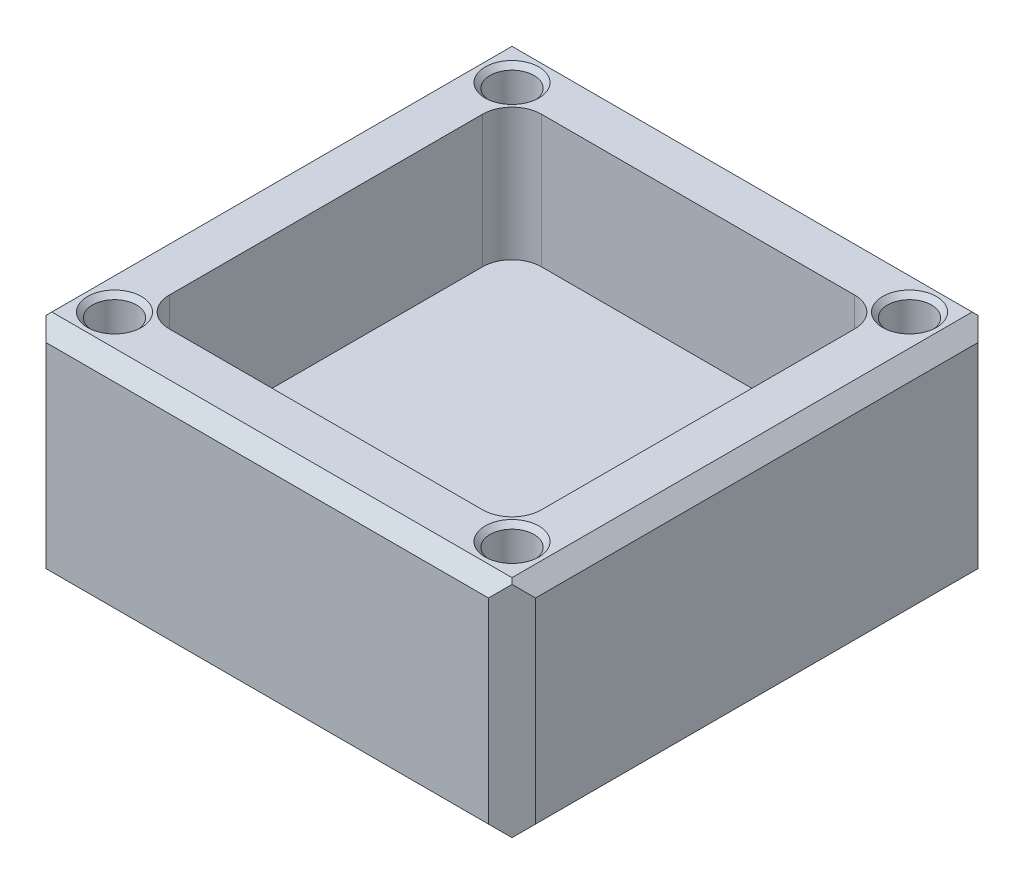
SolidWorks part; units mm, degrees
ref_plane "Front Plane" through (0, 0, 0) normal (0, 0, 1) x (1, 0, 0)
ref_plane "Top Plane" through (0, 0, 0) normal (0, 1, 0) x (1, 0, 0)
ref_plane "Right Plane" through (0, 0, 0) normal (1, 0, 0) x (0, 0, -1)
sketch "Sketch1" plane through (0, 0, 0) normal (0, 0, 1) x (1, 0, 0)
  line L0 (0, -21.5) -> (3.5, -25)
  line L1 (1.5, 0) -> (48.5, 0)
  line L2 (0, -1.5) -> (0, -21.5)
  line L3 (3.5, -25) -> (46.5, -25)
  line L4 (50, -1.5) -> (50, -21.5)
  line L5 (1.5, 0) -> (0, -1.5)
  line L6 (25, -25) -> (25, -15.9605) construction
  line L7 (50, -21.5) -> (46.5, -25)
  line L8 (48.5, 0) -> (50, -1.5)
  dimension "D1" = 47
  dimension "D2" = 20
  dimension "D3" = 2.1213
  dimension "D4" = 4.9497
  dimension "D5" = 43
  dimension "D6" = 50
  dimension "D7" = 0
  dimension "D8" = 50
extrude "Boss-Extrude1" add sketch "Sketch1" along normal blind 50
sketch "Sketch2" plane through (0, 0, 0) normal (-1, 0, 0) x (0, 0, 1)
  line L0 (48.5, 0) -> (50, -1.5)
  line L1 (50, 0) -> (0, 0) construction
  line L2 (50, -1.5) -> (50, -21.5) construction
  line L3 (48.5, 0) -> (50, 0)
  line L4 (50, 0) -> (50, -1.5)
  line L5 (25, -1.5) -> (25, -9.5541) construction
  line L6 (50, -1.5) -> (0, -1.5) construction
  line L7 (50, -21.5) -> (46.5, -25)
  line L8 (50, -25) -> (0, -25) construction
  line L9 (46.5, -25) -> (50, -25)
  line L10 (50, -25) -> (50, -21.5)
  line L11 (1.5, 0) -> (0, 0)
  line L12 (1.5, 0) -> (0, -1.5)
  line L13 (0, 0) -> (0, -1.5)
  line L14 (3.5, -25) -> (0, -25)
  line L15 (0, -21.5) -> (3.5, -25)
  line L16 (0, -25) -> (0, -21.5)
  dimension "D1" = 1.5
  dimension "D2" = 1.5
  dimension "D3" = 3.5
extrude "Cut-Extrude1" cut sketch "Sketch2" against normal blind 50
sketch "Sketch3" plane through (0, 0, 0) normal (0, 1, 0) x (1, 0, 0)
  line L0 (1.5, -48.5) -> (1.5, -1.5) construction
  line L1 (9, -6) -> (41, -6)
  line L2 (6, -9) -> (6, -41)
  line L3 (9, -44) -> (41, -44)
  line L4 (44, -9) -> (44, -41)
  line L5 (6.8787, -6.8787) -> (43.1213, -43.1213) construction
  line L6 (6.8787, -43.1213) -> (43.1213, -6.8787) construction
  line L7 (41, -6) -> (41, -10.4053) construction
  line L9 (48.5, -1.5) -> (1.5, -1.5) construction
  arc A0 (44, -9) -> (41, -6) centre (41, -9) ccw
  arc A1 (41, -44) -> (44, -41) centre (41, -41) ccw
  arc A2 (6, -41) -> (9, -44) centre (9, -41) ccw
  arc A3 (9, -6) -> (6, -9) centre (9, -9) ccw
  point P0 (25, -25)
  point P13 (41, -9)
  point P26 (25, -25)
  dimension "D5" = 3
  dimension "D1" = 4
  dimension "D3" = 4.5
  dimension "D4" = 4.5
  dimension "D6" = 3
extrude "Cut-Extrude2" cut sketch "Sketch3" against normal blind 13.5
sketch "Sketch4" plane through (0, 0, 0) normal (0, 1, 0) x (1, 0, 0)
  line L0 (1.5, -1.5) -> (7.5242, -7.5242) construction
  line L1 (48.5, -1.5) -> (1.5, -1.5) construction
  line L2 (1.5, -48.5) -> (1.5, -1.5) construction
  line L3 (25, -1.5) -> (25, -38.5821) construction
  line L4 (1.5, -25) -> (39.9662, -25) construction
  circle A0 centre (4.7, -4.7) radius 2.25
  circle A1 centre (45.3, -4.7) radius 2.25
  circle A2 centre (45.3, -45.3) radius 2.25
  circle A3 centre (4.7, -45.3) radius 2.25
  point P22 (25, -25)
  dimension "D3" = 4.5
  dimension "D1" = 3.2
  dimension "D2" = 3.2
  dimension "D4" = 4
extrude "Cut-Extrude3" cut sketch "Sketch4" against normal blind 18
hole_wizard "CSK for M2.5 Countersunk Flat Head Screw1" positions "3DSketch2" profile "Sketch6" countersink size "M2.5" standard "ISO"
sketch3d "3DSketch2"
  line L0 (4.7, -18, 4.7) -> (4.7, 0, 4.7) construction
  line L1 (45.3, -18, 4.7) -> (45.3, 0, 4.7) construction
  line L2 (45.3, -18, 45.3) -> (45.3, 0, 45.3) construction
  line L3 (4.7, -18, 45.3) -> (4.7, 0, 45.3) construction
  point P0 (4.7, 0, 4.7)
  point P4 (45.3, 0, 4.7)
  point P8 (45.3, 0, 45.3)
  point P12 (4.7, 0, 45.3)
sketch "Sketch6" plane through (4.7, 0, 4.7) normal (1, 0, 0) x (0, 0, 1)
  line L0 (0, 0) -> (0, 1.72)
  line L1 (0, 1.72) -> (1.45, 0.8488)
  line L2 (1.45, 0.8488) -> (1.45, 1.3)
  line L3 (1.45, 1.3) -> (2.75, 0)
  line L5 (2.75, 0) -> (0, 0)
  line L6 (-1.45, 1.3) -> (-2.75, 0) construction
  line L10 (0, 1.72) -> (-1.45, 0.8488) construction
  line L11 (0, -6.35) -> (0, 107.95) construction
  dimension "Hole Dia." = 2.9
  dimension "Hole Depth" = 1.72
  dimension "Near C'Sink Dia." = 5.5
  dimension "Near C'Sink Angle" = 90
  dimension "Drill Angle" = 118
sketch "Sketch7" plane through (0, 0, 0) normal (0, 1, 0) x (1, 0, 0)
  line L0 (0, -2.4042) -> (2.4042, 0)
  line L1 (0, -50) -> (0, 0) construction
  line L2 (50, 0) -> (0, 0) construction
  line L3 (25, -6) -> (25, -30.3143) construction
  line L4 (41, -6) -> (9, -6) construction
  line L5 (6, -25) -> (36.2639, -25) construction
  line L6 (6, -9) -> (6, -41) construction
  line L7 (2.4042, 0) -> (0, 0)
  line L8 (0, 0) -> (0, -2.4042)
  line L9 (50, 0) -> (47.5958, 0)
  line L10 (47.5958, 0) -> (50, -2.4042)
  line L11 (50, -2.4042) -> (50, 0)
  line L12 (50, -50) -> (50, -47.5958)
  line L13 (50, -47.5958) -> (47.5958, -50)
  line L14 (47.5958, -50) -> (50, -50)
  line L15 (0, -50) -> (2.4042, -50)
  line L16 (2.4042, -50) -> (0, -47.5958)
  line L17 (0, -47.5958) -> (0, -50)
  point P15 (25, -25)
  point P17 (2.4042, 0)
  point P30 (25, -25)
  dimension "D1" = 1.7
  dimension "D2" = 4
extrude "Cut-Extrude4" cut sketch "Sketch7" against normal through all
sketch "Sketch9" plane through (0, -25, 0) normal (0, -1, 0) x (1, 0, 0)
  line L0 (7.4157, 33.2878) -> (7.4157, 30.1376)
  line L1 (7.4157, 30.1376) -> (7.9407, 30.1376)
  line L2 (7.9407, 36.438) -> (7.4157, 36.438)
  line L3 (7.4157, 36.438) -> (7.4157, 33.2878)
  line L4 (11.1959, 33.2878) -> (11.1959, 30.1376)
  line L5 (11.1959, 30.1376) -> (12.351, 30.1376)
  line L6 (12.351, 36.438) -> (11.1959, 36.438)
  line L7 (11.1959, 36.438) -> (11.1959, 33.2878)
  line L8 (22.0116, 30.1376) -> (22.5366, 30.1376)
  line L9 (22.5366, 30.1376) -> (22.5366, 33.2878)
  line L10 (22.5366, 33.2878) -> (22.5366, 36.438)
  line L11 (22.5366, 36.438) -> (22.0116, 36.438)
  line L12 (34.0873, 33.2878) -> (34.0873, 30.1376)
  line L13 (34.0873, 30.1376) -> (35.1374, 30.1376)
  line L14 (35.5574, 31.1877) -> (34.9274, 31.1877)
  line L15 (34.9274, 31.1877) -> (34.9274, 33.8128)
  line L16 (39.2502, 30.1376) -> (39.7929, 30.1376)
  line L17 (39.7929, 30.1376) -> (39.7228, 32.6536)
  line L18 (37.6896, 36.3763) -> (36.8175, 36.4933)
  line L19 (36.8175, 36.4933) -> (36.8175, 33.3154)
  line L20 (41.8578, 32.7628) -> (41.8578, 35.3879)
  line L21 (41.8578, 35.3879) -> (42.3828, 35.3879)
  line L22 (43.5379, 33.2878) -> (43.5379, 30.1376)
  line L23 (43.5379, 30.1376) -> (44.693, 30.1376)
  line L24 (44.693, 36.438) -> (43.5379, 36.438)
  line L25 (43.5379, 36.438) -> (43.5379, 33.2878)
  line L26 (4.0555, 23.7322) -> (4.0555, 18.5869)
  line L27 (4.0555, 18.5869) -> (4.8955, 18.5869)
  line L28 (4.8955, 18.5869) -> (5.7356, 18.5869)
  line L29 (5.7356, 18.5869) -> (5.7356, 20.267)
  line L30 (5.7356, 20.267) -> (5.7356, 21.9471)
  line L31 (5.7356, 21.9471) -> (6.8907, 21.9471)
  line L32 (6.8907, 21.9471) -> (8.0457, 21.9471)
  line L33 (8.0457, 21.9471) -> (8.0457, 22.7762)
  line L34 (8.0457, 22.7762) -> (8.0457, 23.6052)
  line L35 (8.0457, 23.6052) -> (6.9432, 23.6687)
  line L36 (6.9432, 23.6687) -> (5.8406, 23.7322)
  line L37 (5.8406, 23.7322) -> (5.7796, 25.4648)
  line L38 (5.7796, 25.4648) -> (5.7186, 27.1974)
  line L39 (5.7186, 27.1974) -> (6.8822, 27.1974)
  line L40 (6.8822, 27.1974) -> (8.0457, 27.1974)
  line L41 (8.0457, 27.1974) -> (8.0457, 28.0375)
  line L42 (8.0457, 28.0375) -> (8.0457, 28.8775)
  line L43 (8.0457, 28.8775) -> (6.0506, 28.8775)
  line L44 (6.0506, 28.8775) -> (4.0555, 28.8775)
  line L45 (4.0555, 28.8775) -> (4.0555, 23.7322)
  line L46 (9.0958, 23.7322) -> (9.0958, 18.5869)
  line L47 (9.0958, 18.5869) -> (9.9358, 18.5869)
  line L48 (9.9358, 18.5869) -> (10.7759, 18.5869)
  line L49 (10.7759, 18.5869) -> (10.7759, 19.5319)
  line L50 (10.7759, 19.5319) -> (10.7759, 20.477)
  line L51 (10.7759, 20.477) -> (11.616, 20.477)
  line L52 (11.616, 20.477) -> (12.456, 20.477)
  line L53 (12.456, 20.477) -> (12.456, 19.5319)
  line L54 (12.456, 19.5319) -> (12.456, 18.5869)
  line L55 (12.456, 18.5869) -> (13.2961, 18.5869)
  line L56 (13.2961, 18.5869) -> (14.1361, 18.5869)
  line L57 (14.1361, 18.5869) -> (14.1361, 22.3341)
  line L58 (10.2178, 28.8775) -> (9.0958, 28.8775)
  line L59 (9.0958, 28.8775) -> (9.0958, 23.7322)
  line L60 (12.351, 24.1833) -> (12.351, 22.2621)
  line L61 (12.351, 22.2621) -> (11.616, 22.2621)
  line L62 (11.616, 22.2621) -> (10.8809, 22.2621)
  line L63 (10.8809, 22.2621) -> (10.8215, 24.6248)
  line L64 (22.7352, 20.013) -> (22.0344, 21.0296)
  line L65 (22.0344, 21.0296) -> (21.1829, 20.736)
  line L66 (22.0199, 25.8088) -> (22.2151, 26.0638)
  line L67 (22.2151, 26.0638) -> (22.4449, 26.3632)
  line L68 (22.4449, 26.3632) -> (22.7061, 26.7026)
  line L69 (24.6367, 27.1974) -> (25.2668, 27.1974)
  line L70 (25.2668, 27.1974) -> (25.2668, 22.8922)
  line L71 (25.2668, 22.8922) -> (25.2668, 18.5869)
  line L72 (25.2668, 18.5869) -> (26.1068, 18.5869)
  line L73 (26.1068, 18.5869) -> (26.9469, 18.5869)
  line L74 (26.9469, 18.5869) -> (26.9469, 22.8922)
  line L75 (26.9469, 22.8922) -> (26.9469, 27.1974)
  line L76 (26.9469, 27.1974) -> (27.6819, 27.1974)
  line L77 (28.417, 28.0375) -> (28.417, 28.8775)
  line L78 (28.417, 28.8775) -> (26.2118, 28.8775)
  line L79 (26.2118, 28.8775) -> (24.0067, 28.8775)
  line L80 (24.0067, 28.8775) -> (24.0067, 28.0375)
  line L81 (33.1744, 19.4939) -> (33.8773, 20.2608)
  line L82 (33.8773, 20.2608) -> (33.8773, 23.6345)
  line L83 (32.1506, 23.5986) -> (32.0922, 20.582)
  line L84 (32.0922, 20.582) -> (31.4622, 20.582)
  line L85 (31.4622, 20.582) -> (30.8321, 20.582)
  line L86 (30.8321, 20.582) -> (30.7737, 23.5986)
  line L87 (35.1374, 23.7322) -> (35.1374, 18.5869)
  line L88 (35.1374, 18.5869) -> (35.9774, 18.5869)
  line L89 (35.9774, 18.5869) -> (36.8175, 18.5869)
  line L90 (36.8175, 18.5869) -> (36.8175, 20.5874)
  line L91 (36.8175, 20.5874) -> (36.8175, 22.5879)
  line L92 (36.8175, 22.5879) -> (37.4221, 22.2753)
  line L93 (38.2876, 19.9348) -> (38.2876, 18.5869)
  line L94 (38.2876, 18.5869) -> (39.1492, 18.5869)
  line L95 (39.1492, 18.5869) -> (40.0108, 18.5869)
  line L96 (40.0108, 18.5869) -> (39.9367, 20.3546)
  line L97 (39.4148, 22.7279) -> (38.9669, 23.3336)
  line L98 (38.9669, 23.3336) -> (39.4038, 23.9333)
  line L99 (36.6179, 28.8775) -> (35.1374, 28.8775)
  line L100 (35.1374, 28.8775) -> (35.1374, 23.7322)
  line L101 (42.4878, 21.0243) -> (42.4878, 18.5869)
  line L102 (42.4878, 18.5869) -> (43.3279, 18.5869)
  line L103 (43.3279, 18.5869) -> (44.1679, 18.5869)
  line L104 (44.1679, 18.5869) -> (44.1679, 21.0929)
  line L105 (45.8473, 27.0399) -> (45.8481, 28.8775)
  line L106 (45.8481, 28.8775) -> (45.008, 28.8775)
  line L107 (45.008, 28.8775) -> (44.1679, 28.8775)
  line L108 (44.1679, 28.8775) -> (44.1679, 27.2394)
  line L109 (42.6273, 27.3138) -> (42.7595, 28.8775)
  line L110 (42.7595, 28.8775) -> (41.7836, 28.8775)
  line L111 (41.7836, 28.8775) -> (40.8077, 28.8775)
  line L112 (40.8077, 28.8775) -> (40.8077, 27.2957)
  arc A0 (4.2655, 35.913) -> (4.2879, 35.6646) centre (5.6564, 35.913) ccw
  arc A1 (4.2879, 35.6646) -> (4.36, 35.5061) centre (4.6375, 35.728) ccw
  arc A2 (4.36, 35.5061) -> (4.4891, 35.4179) centre (4.5688, 35.6731) ccw
  arc A3 (4.4891, 35.4179) -> (4.6855, 35.3879) centre (4.6855, 36.0471) ccw
  arc A4 (4.9174, 35.2815) -> (4.6855, 35.3879) centre (4.6855, 35.0821) ccw
  arc A5 (5.0446, 35.0073) -> (4.9174, 35.2815) centre (4.4965, 34.9196) ccw
  arc A6 (5.0963, 34.4011) -> (5.0446, 35.0073) centre (0.9638, 34.3543) ccw
  arc A7 (5.1056, 32.7628) -> (5.0963, 34.4011) centre (-139.7772, 32.7628) ccw
  arc A8 (5.1056, 32.7628) -> (5.1148, 31.1245) centre (149.9883, 32.7627) ccw
  arc A9 (5.1148, 31.1245) -> (5.1665, 30.5182) centre (9.2473, 31.1712) ccw
  arc A10 (5.1665, 30.5182) -> (5.2937, 30.244) centre (5.7146, 30.6059) ccw
  arc A11 (5.2937, 30.244) -> (5.5256, 30.1376) centre (5.5256, 30.4434) ccw
  arc A12 (5.5256, 30.1376) -> (5.7574, 30.244) centre (5.5256, 30.4434) ccw
  arc A13 (5.7574, 30.244) -> (5.8847, 30.5182) centre (5.3366, 30.6059) ccw
  arc A14 (5.8847, 30.5182) -> (5.9363, 31.1245) centre (1.8038, 31.1712) ccw
  arc A15 (5.9363, 31.1245) -> (5.9456, 32.7628) centre (-138.9372, 32.7627) ccw
  arc A16 (5.9549, 34.4011) -> (5.9456, 32.7628) centre (150.8284, 32.7628) ccw
  arc A17 (6.0065, 35.0073) -> (5.9549, 34.4011) centre (10.0874, 34.3543) ccw
  arc A18 (6.1338, 35.2815) -> (6.0065, 35.0073) centre (6.5546, 34.9196) ccw
  arc A19 (6.3656, 35.3879) -> (6.1338, 35.2815) centre (6.3656, 35.0821) ccw
  arc A20 (6.3656, 35.3879) -> (6.562, 35.4179) centre (6.3656, 36.0471) ccw
  arc A21 (6.562, 35.4179) -> (6.6911, 35.5061) centre (6.4824, 35.6731) ccw
  arc A22 (6.6911, 35.5061) -> (6.7633, 35.6646) centre (6.4137, 35.728) ccw
  arc A23 (6.7633, 35.6646) -> (6.7857, 35.913) centre (5.3947, 35.913) ccw
  arc A24 (6.7857, 35.913) -> (6.7415, 36.2145) centre (5.7341, 35.913) ccw
  arc A25 (6.7415, 36.2145) -> (6.6071, 36.3636) centre (6.517, 36.1473) ccw
  arc A26 (6.6071, 36.3636) -> (6.3156, 36.4264) centre (6.2915, 35.606) ccw
  arc A27 (6.3156, 36.4264) -> (5.5256, 36.438) centre (5.5256, 9.5402) ccw
  arc A28 (5.5256, 36.438) -> (4.7356, 36.4264) centre (5.5256, 9.5402) ccw
  arc A29 (4.7356, 36.4264) -> (4.444, 36.3636) centre (4.7597, 35.606) ccw
  arc A30 (4.444, 36.3636) -> (4.3097, 36.2145) centre (4.5341, 36.1473) ccw
  arc A31 (4.3097, 36.2145) -> (4.2655, 35.913) centre (5.3171, 35.913) ccw
  arc A32 (7.9407, 30.1376) -> (8.1402, 30.149) centre (7.9407, 31.8909) ccw
  arc A33 (8.1402, 30.149) -> (8.3042, 30.1839) centre (8.0402, 31.0223) ccw
  arc A34 (8.3042, 30.1839) -> (8.4135, 30.2346) centre (8.1642, 30.6284) ccw
  arc A35 (8.4135, 30.2346) -> (8.4409, 30.2951) centre (8.3812, 30.2857) ccw
  arc A36 (8.4317, 30.4087) -> (8.4409, 30.2951) centre (9.182, 30.4121) ccw
  arc A37 (8.4306, 30.8845) -> (8.4317, 30.4087) centre (112.6728, 30.8845) ccw
  arc A38 (8.4332, 31.4452) -> (8.4306, 30.8845) centre (70.4294, 30.8845) ccw
  arc A39 (8.4409, 32.0802) -> (8.4332, 31.4452) centre (110.2733, 30.5242) ccw
  arc A40 (8.4672, 33.1306) -> (8.4409, 32.0802) centre (62.4616, 31.2548) ccw
  arc A41 (8.5327, 33.4901) -> (8.4672, 33.1306) centre (9.7261, 33.0868) ccw
  arc A42 (8.6871, 33.6512) -> (8.5327, 33.4901) centre (8.7818, 33.4059) ccw
  arc A43 (8.9908, 33.7078) -> (8.6871, 33.6512) centre (8.9908, 32.8647) ccw
  arc A44 (9.2953, 33.6469) -> (8.9908, 33.7078) centre (8.9908, 32.9159) ccw
  arc A45 (9.4479, 33.4768) -> (9.2953, 33.6469) centre (9.1932, 33.4019) ccw
  arc A46 (9.5063, 33.0931) -> (9.4479, 33.4768) centre (8.0635, 33.0696) ccw
  arc A47 (9.5158, 31.9227) -> (9.5063, 33.0931) centre (-62.5724, 31.9227) ccw
  arc A48 (9.5158, 31.9227) -> (9.5264, 30.8445) centre (64.7115, 31.9227) ccw
  arc A49 (9.5264, 30.8445) -> (9.5807, 30.4132) centre (11.5843, 30.8847) ccw
  arc A50 (9.5807, 30.4132) -> (9.7087, 30.2148) centre (9.9233, 30.4939) ccw
  arc A51 (9.7087, 30.2148) -> (9.9358, 30.1376) centre (9.9358, 30.5101) ccw
  arc A52 (9.9358, 30.1376) -> (10.1706, 30.2601) centre (9.9358, 30.4237) ccw
  arc A53 (10.1706, 30.2601) -> (10.2964, 30.5839) centre (9.5664, 30.6812) ccw
  arc A54 (10.2964, 30.5839) -> (10.347, 31.2991) centre (4.5452, 31.3507) ccw
  arc A55 (10.347, 31.2991) -> (10.3559, 33.2878) centre (-213.3931, 33.2876) ccw
  arc A56 (10.3559, 33.2878) -> (10.347, 35.2764) centre (-213.3931, 33.2879) ccw
  arc A57 (10.347, 35.2764) -> (10.2964, 35.9917) centre (4.5452, 35.2249) ccw
  arc A58 (10.2964, 35.9917) -> (10.1706, 36.3155) centre (9.5664, 35.8944) ccw
  arc A59 (10.1706, 36.3155) -> (9.9358, 36.438) centre (9.9358, 36.1519) ccw
  arc A60 (9.9358, 36.438) -> (9.7221, 36.3978) centre (9.9358, 35.8498) ccw
  arc A61 (9.7221, 36.3978) -> (9.5954, 36.2835) centre (9.8097, 36.1731) ccw
  arc A62 (9.5954, 36.2835) -> (9.5319, 36.0581) centre (10.1168, 36.015) ccw
  arc A63 (9.5319, 36.0581) -> (9.5158, 35.6224) centre (15.4425, 35.6224) ccw
  arc A64 (9.4968, 35.1699) -> (9.5158, 35.6224) centre (4.1141, 35.6224) ccw
  arc A65 (9.4231, 34.9332) -> (9.4968, 35.1699) centre (8.9266, 35.2178) ccw
  arc A66 (9.2705, 34.7949) -> (9.4231, 34.9332) centre (9.1335, 35.0992) ccw
  arc A67 (8.9908, 34.7065) -> (9.2705, 34.7949) centre (8.7551, 35.9395) ccw
  arc A68 (8.6844, 34.6775) -> (8.9908, 34.7065) centre (8.6847, 36.3077) ccw
  arc A69 (8.5426, 34.7549) -> (8.6844, 34.6775) centre (8.6844, 34.8462) ccw
  arc A70 (8.478, 34.9583) -> (8.5426, 34.7549) centre (8.886, 34.976) ccw
  arc A71 (8.4658, 35.522) -> (8.478, 34.9583) centre (21.4789, 35.522) ccw
  arc A72 (8.4658, 35.522) -> (8.4511, 36.0639) centre (-1.5571, 35.522) ccw
  arc A73 (8.4511, 36.0639) -> (8.3832, 36.2939) centre (7.9331, 36.0359) ccw
  arc A74 (8.3832, 36.2939) -> (8.2352, 36.404) centre (8.1826, 36.1789) ccw
  arc A75 (8.2352, 36.404) -> (7.9407, 36.438) centre (7.9407, 35.1441) ccw
  arc A76 (12.351, 30.1376) -> (13.0651, 30.1499) centre (12.351, 50.8633) ccw
  arc A77 (13.0651, 30.1499) -> (13.3381, 30.214) centre (13.0403, 30.8689) ccw
  arc A78 (13.3381, 30.214) -> (13.4651, 30.3625) centre (13.2424, 30.4244) ccw
  arc A79 (13.4651, 30.3625) -> (13.5061, 30.6626) centre (12.3857, 30.6626) ccw
  arc A80 (13.5061, 30.6626) -> (13.4769, 30.9487) centre (12.0863, 30.6626) ccw
  arc A81 (13.4769, 30.9487) -> (13.3801, 31.0977) centre (13.2387, 30.8997) ccw
  arc A82 (13.3801, 31.0977) -> (13.1838, 31.17) centre (13.1499, 30.7754) ccw
  arc A83 (13.1838, 31.17) -> (12.771, 31.1877) centre (12.771, 26.3667) ccw
  arc A84 (12.3071, 31.2099) -> (12.771, 31.1877) centre (12.771, 36.0343) ccw
  arc A85 (12.1293, 31.3077) -> (12.3071, 31.2099) centre (12.3316, 31.465) ccw
  arc A86 (12.0507, 31.52) -> (12.1293, 31.3077) centre (12.4255, 31.538) ccw
  arc A87 (12.036, 32.1327) -> (12.0507, 31.52) centre (24.7862, 32.1327) ccw
  arc A88 (12.0507, 32.7454) -> (12.036, 32.1327) centre (24.7862, 32.1327) ccw
  arc A89 (12.1293, 32.9578) -> (12.0507, 32.7454) centre (12.4255, 32.7274) ccw
  arc A90 (12.3071, 33.0555) -> (12.1293, 32.9578) centre (12.3316, 32.8004) ccw
  arc A91 (12.771, 33.0778) -> (12.3071, 33.0555) centre (12.771, 28.2312) ccw
  arc A92 (12.771, 33.0778) -> (13.1838, 33.0955) centre (12.771, 37.8987) ccw
  arc A93 (13.1838, 33.0955) -> (13.3801, 33.1678) centre (13.1499, 33.49) ccw
  arc A94 (13.3801, 33.1678) -> (13.4769, 33.3167) centre (13.2387, 33.3657) ccw
  arc A95 (13.4769, 33.3167) -> (13.5061, 33.6028) centre (12.0863, 33.6028) ccw
  arc A96 (13.5061, 33.6028) -> (13.4769, 33.8889) centre (12.0863, 33.6028) ccw
  arc A97 (13.4769, 33.8889) -> (13.3801, 34.0378) centre (13.2387, 33.8399) ccw
  arc A98 (13.3801, 34.0378) -> (13.1838, 34.1101) centre (13.1499, 33.7156) ccw
  arc A99 (13.1838, 34.1101) -> (12.771, 34.1278) centre (12.771, 29.3069) ccw
  arc A100 (12.3382, 34.1463) -> (12.771, 34.1278) centre (12.771, 39.2022) ccw
  arc A101 (12.1497, 34.2253) -> (12.3382, 34.1463) centre (12.3666, 34.4784) ccw
  arc A102 (12.0594, 34.3925) -> (12.1497, 34.2253) centre (12.322, 34.4264) ccw
  arc A103 (12.0594, 35.1233) -> (12.0594, 34.3925) centre (14.8915, 34.7579) ccw
  arc A104 (12.1497, 35.2904) -> (12.0594, 35.1233) centre (12.322, 35.0894) ccw
  arc A105 (12.3382, 35.3694) -> (12.1497, 35.2904) centre (12.3666, 35.0374) ccw
  arc A106 (12.771, 35.3879) -> (12.3382, 35.3694) centre (12.771, 30.3135) ccw
  arc A107 (12.771, 35.3879) -> (13.1838, 35.4056) centre (12.771, 40.2088) ccw
  arc A108 (13.1838, 35.4056) -> (13.3801, 35.4779) centre (13.1499, 35.8001) ccw
  arc A109 (13.3801, 35.4779) -> (13.4769, 35.6269) centre (13.2387, 35.6759) ccw
  arc A110 (13.4769, 35.6269) -> (13.5061, 35.913) centre (12.0863, 35.913) ccw
  arc A111 (13.5061, 35.913) -> (13.4651, 36.2131) centre (12.3857, 35.9129) ccw
  arc A112 (13.4651, 36.2131) -> (13.3381, 36.3616) centre (13.2424, 36.1512) ccw
  arc A113 (13.3381, 36.3616) -> (13.0651, 36.4257) centre (13.0403, 35.7066) ccw
  arc A114 (13.0651, 36.4257) -> (12.351, 36.438) centre (12.351, 15.7122) ccw
  arc A115 (17.0763, 36.2869) -> (16.5112, 35.9699) centre (17.747, 34.4291) ccw
  arc A116 (16.5112, 35.9699) -> (16.2014, 35.5312) centre (17.1194, 35.2116) ccw
  arc A117 (16.2014, 35.5312) -> (16.0594, 34.7904) centre (18.655, 34.677) ccw
  arc A118 (16.0594, 34.7904) -> (16.0262, 33.2705) centre (50.8508, 33.2705) ccw
  arc A119 (16.0262, 33.2705) -> (16.0384, 31.8317) centre (100.843, 33.2706) ccw
  arc A120 (16.0384, 31.8317) -> (16.1017, 31.2572) centre (19.1605, 31.8847) ccw
  arc A121 (16.1017, 31.2572) -> (16.2598, 30.9024) centre (16.9855, 31.4385) ccw
  arc A122 (16.2598, 30.9024) -> (16.5796, 30.5729) centre (17.6421, 31.9237) ccw
  arc A123 (16.5796, 30.5729) -> (16.8209, 30.4063) centre (18.0345, 32.4225) ccw
  arc A124 (16.8209, 30.4063) -> (17.0882, 30.2655) centre (18.1883, 32.678) ccw
  arc A125 (17.0882, 30.2655) -> (17.3417, 30.1676) centre (18.039, 32.3505) ccw
  arc A126 (17.3417, 30.1676) -> (17.5342, 30.1376) centre (17.5342, 30.7702) ccw
  arc A127 (17.5342, 30.1376) -> (18.0071, 30.2786) centre (17.5342, 31.0014) ccw
  arc A128 (18.0071, 30.2786) -> (18.4854, 30.6987) centre (16.7702, 32.1692) ccw
  arc A129 (18.4854, 30.6987) -> (18.8445, 31.2565) centre (16.6391, 32.2816) ccw
  arc A130 (18.8445, 31.2565) -> (18.9664, 31.8082) centre (17.6576, 31.8082) ccw
  arc A131 (18.9664, 31.8082) -> (18.9464, 32.151) centre (16.0143, 31.8082) ccw
  arc A132 (18.9464, 32.151) -> (18.8719, 32.3295) centre (18.5975, 32.1102) ccw
  arc A133 (18.8719, 32.3295) -> (18.7243, 32.4201) centre (18.6725, 32.1702) ccw
  arc A134 (18.7243, 32.4201) -> (18.4553, 32.4477) centre (18.4553, 31.1228) ccw
  arc A135 (18.4553, 32.4477) -> (18.1985, 32.419) centre (18.4553, 31.287) ccw
  arc A136 (18.1985, 32.419) -> (18.0356, 32.3291) centre (18.2727, 32.092) ccw
  arc A137 (18.0356, 32.3291) -> (17.9354, 32.159) centre (18.3144, 32.0503) ccw
  arc A138 (17.9354, 32.159) -> (17.8778, 31.8702) centre (19.656, 31.6656) ccw
  arc A139 (17.8238, 31.6012) -> (17.8778, 31.8702) centre (16.2467, 32.0579) ccw
  arc A140 (17.7299, 31.4257) -> (17.8238, 31.6012) centre (17.3631, 31.7346) ccw
  arc A141 (17.5883, 31.327) -> (17.7299, 31.4257) centre (17.4756, 31.6399) ccw
  arc A142 (17.3913, 31.2927) -> (17.5883, 31.327) centre (17.3913, 31.874) ccw
  arc A143 (17.1629, 31.3775) -> (17.3913, 31.2927) centre (17.3913, 31.6426) ccw
  arc A144 (17.0349, 31.5942) -> (17.1629, 31.3775) centre (17.4195, 31.6753) ccw
  arc A145 (16.9814, 32.0687) -> (17.0349, 31.5942) centre (19.4826, 32.1103) ccw
  arc A146 (16.9713, 33.2849) -> (16.9814, 32.0687) centre (90.1362, 33.2849) ccw
  arc A147 (16.9827, 34.4324) -> (16.9713, 33.2849) centre (74.4539, 33.2849) ccw
  arc A148 (17.0358, 34.9534) -> (16.9827, 34.4324) centre (20.1973, 34.3682) ccw
  arc A149 (17.1509, 35.2217) -> (17.0358, 34.9534) centre (17.6871, 34.8329) ccw
  arc A150 (17.3537, 35.3508) -> (17.1509, 35.2217) centre (17.4155, 35.0298) ccw
  arc A151 (17.5245, 35.353) -> (17.3537, 35.3508) centre (17.4453, 34.8751) ccw
  arc A152 (17.6673, 35.2929) -> (17.5245, 35.353) centre (17.4699, 35.0239) ccw
  arc A153 (17.7769, 35.1691) -> (17.6673, 35.2929) centre (17.4362, 34.9779) ccw
  arc A154 (17.8507, 34.9862) -> (17.7769, 35.1691) centre (17.1022, 34.7904) ccw
  arc A155 (17.8507, 34.9862) -> (18.0719, 34.6648) centre (18.4056, 35.1313) ccw
  arc A156 (18.0719, 34.6648) -> (18.4657, 34.5303) centre (18.4926, 35.253) ccw
  arc A157 (18.4657, 34.5303) -> (18.8194, 34.6443) centre (18.4859, 35.0735) ccw
  arc A158 (18.8194, 34.6443) -> (18.9664, 34.9446) centre (18.586, 34.9446) ccw
  arc A159 (18.9664, 34.9446) -> (18.7946, 35.5194) centre (17.9188, 34.9446) ccw
  arc A160 (18.7946, 35.5194) -> (18.3072, 36.0251) centre (17.2092, 34.479) ccw
  arc A161 (18.3072, 36.0251) -> (17.6708, 36.3175) centre (17.2161, 34.4887) ccw
  arc A162 (17.6708, 36.3175) -> (17.0763, 36.2869) centre (17.4238, 35.3242) ccw
  arc A163 (19.5964, 33.2878) -> (19.6053, 31.2991) centre (243.3454, 33.2876) ccw
  arc A164 (19.6053, 31.2991) -> (19.6559, 30.5839) centre (25.4071, 31.3507) ccw
  arc A165 (19.6559, 30.5839) -> (19.7817, 30.2601) centre (20.386, 30.6812) ccw
  arc A166 (19.7817, 30.2601) -> (20.0165, 30.1376) centre (20.0165, 30.4237) ccw
  arc A167 (20.0165, 30.1376) -> (20.2436, 30.2148) centre (20.0165, 30.5101) ccw
  arc A168 (20.2436, 30.2148) -> (20.3716, 30.4132) centre (20.029, 30.4939) ccw
  arc A169 (20.3716, 30.4132) -> (20.426, 30.8445) centre (18.368, 30.8847) ccw
  arc A170 (20.426, 30.8445) -> (20.4365, 31.9227) centre (-34.7592, 31.9227) ccw
  arc A171 (20.446, 33.0931) -> (20.4365, 31.9227) centre (92.5248, 31.9227) ccw
  arc A172 (20.5044, 33.4768) -> (20.446, 33.0931) centre (21.8888, 33.0696) ccw
  arc A173 (20.657, 33.6469) -> (20.5044, 33.4768) centre (20.7591, 33.4019) ccw
  arc A174 (20.9615, 33.7078) -> (20.657, 33.6469) centre (20.9615, 32.9159) ccw
  arc A175 (21.266, 33.6469) -> (20.9615, 33.7078) centre (20.9615, 32.9159) ccw
  arc A176 (21.4186, 33.4768) -> (21.266, 33.6469) centre (21.164, 33.4019) ccw
  arc A177 (21.4771, 33.0931) -> (21.4186, 33.4768) centre (20.0343, 33.0696) ccw
  arc A178 (21.4866, 31.9227) -> (21.4771, 33.0931) centre (-50.6017, 31.9227) ccw
  arc A179 (21.4866, 31.9227) -> (21.4961, 30.7523) centre (93.5748, 31.9227) ccw
  arc A180 (21.4961, 30.7523) -> (21.5545, 30.3686) centre (22.9388, 30.7758) ccw
  arc A181 (21.5545, 30.3686) -> (21.7071, 30.1985) centre (21.8092, 30.4435) ccw
  arc A182 (21.7071, 30.1985) -> (22.0116, 30.1376) centre (22.0116, 30.9295) ccw
  arc A183 (22.0116, 36.438) -> (21.72, 36.4061) centre (22.0116, 35.0883) ccw
  arc A184 (21.72, 36.4061) -> (21.5719, 36.3015) centre (21.7707, 36.1772) ccw
  arc A185 (21.5719, 36.3015) -> (21.5023, 36.0855) centre (21.9654, 36.0555) ccw
  arc A186 (21.5023, 36.0855) -> (21.4866, 35.5979) centre (29.0402, 35.5979) ccw
  arc A187 (21.4708, 35.1104) -> (21.4866, 35.5979) centre (13.9329, 35.5979) ccw
  arc A188 (21.4012, 34.8944) -> (21.4708, 35.1104) centre (21.0077, 35.1403) ccw
  arc A189 (21.2531, 34.7897) -> (21.4012, 34.8944) centre (21.2025, 35.0186) ccw
  arc A190 (20.9615, 34.7579) -> (21.2531, 34.7897) centre (20.9615, 36.1076) ccw
  arc A191 (20.6699, 34.7897) -> (20.9615, 34.7579) centre (20.9615, 36.1076) ccw
  arc A192 (20.5218, 34.8944) -> (20.6699, 34.7897) centre (20.7206, 35.0186) ccw
  arc A193 (20.4522, 35.1104) -> (20.5218, 34.8944) centre (20.9153, 35.1403) ccw
  arc A194 (20.4365, 35.5979) -> (20.4522, 35.1104) centre (27.9901, 35.5979) ccw
  arc A195 (20.4365, 35.5979) -> (20.4208, 36.0496) centre (13.9361, 35.5979) ccw
  arc A196 (20.4208, 36.0496) -> (20.3577, 36.2805) centre (19.8111, 36.0072) ccw
  arc A197 (20.3577, 36.2805) -> (20.231, 36.3969) centre (20.1417, 36.1725) ccw
  arc A198 (20.231, 36.3969) -> (20.0165, 36.438) centre (20.0165, 35.8577) ccw
  arc A199 (20.0165, 36.438) -> (19.7817, 36.3155) centre (20.0165, 36.1519) ccw
  arc A200 (19.7817, 36.3155) -> (19.6559, 35.9917) centre (20.386, 35.8944) ccw
  arc A201 (19.6559, 35.9917) -> (19.6053, 35.2764) centre (25.4071, 35.2249) ccw
  arc A202 (19.6053, 35.2764) -> (19.5964, 33.2878) centre (243.3454, 33.2879) ccw
  arc A203 (24.0562, 36.2203) -> (23.8589, 36.1075) centre (24.3652, 35.4511) ccw
  arc A204 (23.8589, 36.1075) -> (23.6595, 35.9255) centre (24.8555, 34.8154) ccw
  arc A205 (23.6595, 35.9255) -> (23.4878, 35.7073) centre (24.9107, 34.7642) ccw
  arc A206 (23.4878, 35.7073) -> (23.3736, 35.4849) centre (24.4284, 35.0839) ccw
  arc A207 (23.3736, 35.4849) -> (23.213, 34.7296) centre (25.7292, 34.5893) ccw
  arc A208 (23.213, 34.7296) -> (23.1728, 33.2885) centre (49.1417, 33.2843) ccw
  arc A209 (23.1728, 33.2885) -> (23.2125, 31.8474) centre (49.1507, 33.2843) ccw
  arc A210 (23.2125, 31.8474) -> (23.3729, 31.0926) centre (25.7244, 31.9866) ccw
  arc A211 (23.3729, 31.0926) -> (23.6396, 30.6887) centre (24.408, 31.4861) ccw
  arc A212 (23.6396, 30.6887) -> (24.0873, 30.3744) centre (24.8705, 31.9661) ccw
  arc A213 (24.0873, 30.3744) -> (24.6072, 30.2126) centre (24.8633, 31.9515) ccw
  arc A214 (24.6072, 30.2126) -> (25.0833, 30.251) centre (24.762, 31.2633) ccw
  arc A215 (25.0833, 30.251) -> (25.627, 30.5444) centre (24.5819, 31.8308) ccw
  arc A216 (25.627, 30.5444) -> (25.9319, 30.9837) centre (25.0204, 31.2909) ccw
  arc A217 (25.9319, 30.9837) -> (26.0735, 31.7438) centre (23.3249, 31.8625) ccw
  arc A218 (26.0735, 31.7438) -> (26.1068, 33.2875) centre (-9.6709, 33.2876) ccw
  arc A219 (26.1068, 33.2875) -> (26.0947, 34.7391) centre (-60.6695, 33.2875) ccw
  arc A220 (26.0947, 34.7391) -> (26.0316, 35.3165) centre (22.939, 34.6863) ccw
  arc A221 (26.0316, 35.3165) -> (25.8734, 35.6726) centre (25.145, 35.1359) ccw
  arc A222 (25.8734, 35.6726) -> (25.5535, 36.0027) centre (24.4946, 34.6565) ccw
  arc A223 (25.5535, 36.0027) -> (25.1437, 36.2884) centre (22.8728, 32.5948) ccw
  arc A224 (25.1437, 36.2884) -> (24.8439, 36.3971) centre (24.7305, 35.6162) ccw
  arc A225 (24.8439, 36.3971) -> (24.5265, 36.3779) centre (24.7314, 35.6224) ccw
  arc A226 (24.5265, 36.3779) -> (24.0562, 36.2203) centre (25.635, 32.2904) ccw
  arc A227 (25.1516, 32.0296) -> (25.1618, 33.2849) centre (-51.9867, 33.2849) ccw
  arc A228 (25.0951, 31.5645) -> (25.1516, 32.0296) centre (22.909, 32.0661) ccw
  arc A229 (24.954, 31.3399) -> (25.0951, 31.5645) centre (24.7023, 31.6546) ccw
  arc A230 (24.6893, 31.2256) -> (24.954, 31.3399) centre (24.6123, 31.7671) ccw
  arc A231 (24.4229, 31.2622) -> (24.6893, 31.2256) centre (24.6203, 31.7111) ccw
  arc A232 (24.28, 31.4319) -> (24.4229, 31.2622) centre (24.5241, 31.4924) ccw
  arc A233 (24.2256, 31.8538) -> (24.28, 31.4319) centre (26.0871, 31.8795) ccw
  arc A234 (24.2167, 33.1332) -> (24.2256, 31.8538) centre (116.7427, 33.1332) ccw
  arc A235 (24.2348, 34.4699) -> (24.2167, 33.1332) centre (73.6076, 33.1332) ccw
  arc A236 (24.3219, 35.0443) -> (24.2348, 34.4699) centre (26.5941, 34.406) ccw
  arc A237 (24.5146, 35.2883) -> (24.3219, 35.0443) centre (24.7112, 34.9349) ccw
  arc A238 (24.8365, 35.3398) -> (24.5146, 35.2883) centre (24.7464, 34.8717) ccw
  arc A239 (25.0023, 35.2126) -> (24.8365, 35.3398) centre (24.7924, 35.1106) ccw
  arc A240 (25.0991, 34.905) -> (25.0023, 35.2126) centre (24.017, 34.7338) ccw
  arc A241 (25.1495, 34.3466) -> (25.0991, 34.905) centre (20.9577, 34.2495) ccw
  arc A242 (25.1618, 33.2849) -> (25.1495, 34.3466) centre (-20.6999, 33.2849) ccw
  arc A243 (27.6264, 36.2203) -> (27.4291, 36.1075) centre (27.9354, 35.4511) ccw
  arc A244 (27.4291, 36.1075) -> (27.2297, 35.9255) centre (28.4257, 34.8154) ccw
  arc A245 (27.2297, 35.9255) -> (27.058, 35.7073) centre (28.4809, 34.7642) ccw
  arc A246 (27.058, 35.7073) -> (26.9438, 35.4849) centre (27.9986, 35.0839) ccw
  arc A247 (26.9438, 35.4849) -> (26.773, 34.668) centre (29.4358, 34.5374) ccw
  arc A248 (26.773, 34.668) -> (26.7469, 33.1752) centre (50.4404, 33.5073) ccw
  arc A249 (26.7469, 33.1752) -> (26.8113, 31.6869) centre (52.2272, 33.5323) ccw
  arc A250 (26.8113, 31.6869) -> (27.007, 30.9811) centre (28.6684, 31.8217) ccw
  arc A251 (27.007, 30.9811) -> (27.6567, 30.3345) centre (28.3096, 31.6403) ccw
  arc A252 (27.6567, 30.3345) -> (28.5267, 30.2456) centre (28.2091, 31.4391) ccw
  arc A253 (28.5267, 30.2456) -> (29.2879, 30.7608) centre (28.1672, 31.5967) ccw
  arc A254 (29.2879, 30.7608) -> (29.6372, 31.6811) centre (27.8503, 31.833) ccw
  arc A255 (29.6372, 31.6811) -> (29.6579, 32.0995) centre (23.7652, 32.1803) ccw
  arc A256 (29.6579, 32.0995) -> (29.6138, 32.3073) centre (29.1776, 32.1061) ccw
  arc A257 (29.6138, 32.3073) -> (29.4979, 32.412) centre (29.4334, 32.2241) ccw
  arc A258 (29.4979, 32.412) -> (29.2837, 32.4477) centre (29.2837, 31.7883) ccw
  arc A259 (29.2837, 32.4477) -> (29.0875, 32.4133) centre (29.2837, 31.8725) ccw
  arc A260 (29.0875, 32.4133) -> (28.9462, 32.3145) centre (29.201, 32.1004) ccw
  arc A261 (28.9462, 32.3145) -> (28.8524, 32.1388) centre (29.3146, 32.0049) ccw
  arc A262 (28.8524, 32.1388) -> (28.7985, 31.8702) centre (30.4267, 31.6829) ccw
  arc A263 (28.7407, 31.5978) -> (28.7985, 31.8702) centre (27.3328, 32.0388) ccw
  arc A264 (28.637, 31.4095) -> (28.7407, 31.5978) centre (28.2234, 31.7598) ccw
  arc A265 (28.4775, 31.2896) -> (28.637, 31.4095) centre (28.2939, 31.7002) ccw
  arc A266 (28.2517, 31.2245) -> (28.4775, 31.2896) centre (28.1333, 32.0591) ccw
  arc A267 (27.9802, 31.2604) -> (28.2517, 31.2245) centre (28.1801, 31.7291) ccw
  arc A268 (27.8408, 31.43) -> (27.9802, 31.2604) centre (28.0735, 31.479) ccw
  arc A269 (27.8001, 31.8566) -> (27.8408, 31.43) centre (29.709, 31.8238) ccw
  arc A270 (27.8317, 33.2172) -> (27.8001, 31.8566) centre (140.5273, 29.92) ccw
  arc A271 (27.8778, 34.3889) -> (27.8317, 33.2172) centre (85.6741, 31.5248) ccw
  arc A272 (27.9476, 34.9349) -> (27.8778, 34.3889) centre (31.4275, 34.213) ccw
  arc A273 (28.0699, 35.2187) -> (27.9476, 34.9349) centre (28.6998, 34.7789) ccw
  arc A274 (28.2744, 35.3512) -> (28.0699, 35.2187) centre (28.3352, 35.0335) ccw
  arc A275 (28.4451, 35.3532) -> (28.2744, 35.3512) centre (28.3653, 34.8764) ccw
  arc A276 (28.5879, 35.2929) -> (28.4451, 35.3532) centre (28.3898, 35.0233) ccw
  arc A277 (28.6975, 35.169) -> (28.5879, 35.2929) centre (28.356, 34.9772) ccw
  arc A278 (28.7714, 34.9862) -> (28.6975, 35.169) centre (28.0241, 34.7907) ccw
  arc A279 (28.7714, 34.9862) -> (28.8452, 34.8152) centre (29.3681, 35.1422) ccw
  arc A280 (28.8452, 34.8152) -> (28.9667, 34.6738) centre (29.3704, 35.1437) ccw
  arc A281 (28.9667, 34.6738) -> (29.1188, 34.5802) centre (29.3353, 35.1028) ccw
  arc A282 (29.1188, 34.5802) -> (29.2815, 34.5479) centre (29.2815, 34.973) ccw
  arc A283 (29.2815, 34.5479) -> (29.5847, 34.7061) centre (29.2815, 34.9175) ccw
  arc A284 (29.5847, 34.7061) -> (29.6801, 35.0791) centre (29.1346, 35.0199) ccw
  arc A285 (29.6801, 35.0791) -> (29.5084, 35.5744) centre (28.5156, 34.9528) ccw
  arc A286 (29.5084, 35.5744) -> (29.1237, 36.0027) centre (28.0865, 34.6841) ccw
  arc A287 (29.1237, 36.0027) -> (28.714, 36.2884) centre (26.443, 32.5948) ccw
  arc A288 (28.714, 36.2884) -> (28.4142, 36.3971) centre (28.3007, 35.6162) ccw
  arc A289 (28.4142, 36.3971) -> (28.0967, 36.3779) centre (28.3016, 35.6224) ccw
  arc A290 (28.0967, 36.3779) -> (27.6264, 36.2203) centre (29.2052, 32.2904) ccw
  arc A291 (31.2236, 36.1924) -> (31.0348, 36.072) centre (31.6433, 35.3256) ccw
  arc A292 (31.0348, 36.072) -> (30.8381, 35.8881) centre (32.2916, 34.5304) ccw
  arc A293 (30.8381, 35.8881) -> (30.6635, 35.6742) centre (32.3485, 34.4772) ccw
  arc A294 (30.6635, 35.6742) -> (30.5411, 35.4616) centre (31.7169, 34.9259) ccw
  arc A295 (30.5411, 35.4616) -> (30.3653, 34.7609) centre (32.3596, 34.6331) ccw
  arc A296 (30.3653, 34.7609) -> (30.3136, 33.3216) centre (55.9476, 33.1213) ccw
  arc A297 (30.3136, 33.3216) -> (30.3449, 31.8799) centre (54.7182, 33.131) ccw
  arc A298 (30.3449, 31.8799) -> (30.5071, 31.1091) centre (32.8763, 32.0099) ccw
  arc A299 (30.5071, 31.1091) -> (30.9206, 30.5239) centre (31.8509, 31.62) ccw
  arc A300 (30.9206, 30.5239) -> (31.5587, 30.2232) centre (31.7972, 31.5568) ccw
  arc A301 (31.5587, 30.2232) -> (32.2793, 30.2791) centre (31.8116, 31.6371) ccw
  arc A302 (32.2793, 30.2791) -> (32.9176, 30.6779) centre (31.7344, 31.8611) ccw
  arc A303 (32.9176, 30.6779) -> (33.0822, 30.9523) centre (32.4511, 31.1444) ccw
  arc A304 (33.0822, 30.9523) -> (33.1796, 31.408) centre (30.4526, 31.7526) ccw
  arc A305 (33.1796, 31.408) -> (33.2329, 32.1158) centre (26.2103, 32.2885) ccw
  arc A306 (33.2329, 32.1158) -> (33.2473, 33.2875) centre (-14.3982, 33.2875) ccw
  arc A307 (33.2473, 33.2875) -> (33.2351, 34.7391) centre (-53.5291, 33.2875) ccw
  arc A308 (33.2351, 34.7391) -> (33.172, 35.3165) centre (30.0795, 34.6863) ccw
  arc A309 (33.172, 35.3165) -> (33.0138, 35.6726) centre (32.2855, 35.1359) ccw
  arc A310 (33.0138, 35.6726) -> (32.6939, 36.0027) centre (31.635, 34.6565) ccw
  arc A311 (32.6939, 36.0027) -> (32.2792, 36.2909) centre (30.0591, 32.653) ccw
  arc A312 (32.2792, 36.2909) -> (31.9754, 36.3977) centre (31.8766, 35.6312) ccw
  arc A313 (31.9754, 36.3977) -> (31.663, 36.3688) centre (31.8837, 35.6863) ccw
  arc A314 (31.663, 36.3688) -> (31.2236, 36.1924) centre (32.7179, 33.1062) ccw
  arc A315 (32.2921, 32.0687) -> (32.3022, 33.2849) centre (-40.8627, 33.2849) ccw
  arc A316 (32.2386, 31.5942) -> (32.2921, 32.0687) centre (29.7909, 32.1103) ccw
  arc A317 (32.1106, 31.3775) -> (32.2386, 31.5942) centre (31.854, 31.6753) ccw
  arc A318 (31.8822, 31.2927) -> (32.1106, 31.3775) centre (31.8822, 31.6426) ccw
  arc A319 (31.6542, 31.371) -> (31.8822, 31.2927) centre (31.8822, 31.6636) ccw
  arc A320 (31.5192, 31.5738) -> (31.6542, 31.371) centre (31.8912, 31.6752) ccw
  arc A321 (31.4484, 32.0097) -> (31.5192, 31.5738) centre (33.5524, 32.1278) ccw
  arc A322 (31.4006, 33.0602) -> (31.4484, 32.0097) centre (80.8375, 34.782) ccw
  arc A323 (31.3759, 34.372) -> (31.4006, 33.0602) centre (72.3489, 34.4864) ccw
  arc A324 (31.447, 34.9977) -> (31.3759, 34.372) centre (34.0979, 34.3796) ccw
  arc A325 (31.6299, 35.2779) -> (31.447, 34.9977) centre (31.9233, 34.8867) ccw
  arc A326 (31.9341, 35.3481) -> (31.6299, 35.2779) centre (31.8612, 34.9695) ccw
  arc A327 (32.1275, 35.2191) -> (31.9341, 35.3481) centre (31.8773, 35.0533) ccw
  arc A328 (32.2381, 34.9428) -> (32.1275, 35.2191) centre (31.5157, 34.8139) ccw
  arc A329 (32.2906, 34.4129) -> (32.2381, 34.9428) centre (28.8732, 34.3423) ccw
  arc A330 (32.3022, 33.2849) -> (32.2906, 34.4129) centre (-22.32, 33.2849) ccw
  arc A331 (35.1374, 30.1376) -> (35.7758, 30.1508) centre (35.1374, 45.601) ccw
  arc A332 (35.7758, 30.1508) -> (36.0299, 30.2164) centre (35.7499, 30.7764) ccw
  arc A333 (36.0299, 30.2164) -> (36.1496, 30.3644) centre (35.9272, 30.4218) ccw
  arc A334 (36.1496, 30.3644) -> (36.1875, 30.6626) centre (34.993, 30.6626) ccw
  arc A335 (36.1875, 30.6626) -> (36.1609, 30.9408) centre (34.7189, 30.6626) ccw
  arc A336 (36.1609, 30.9408) -> (36.072, 31.0914) centre (35.9054, 30.8915) ccw
  arc A337 (36.072, 31.0914) -> (35.8963, 31.1672) centre (35.8557, 30.832) ccw
  arc A338 (35.8963, 31.1672) -> (35.5574, 31.1877) centre (35.5574, 28.3657) ccw
  arc A339 (34.9274, 33.8128) -> (34.9181, 35.4511) centre (-109.9554, 33.8129) ccw
  arc A340 (34.9181, 35.4511) -> (34.8665, 36.0573) centre (30.7856, 35.4044) ccw
  arc A341 (34.8665, 36.0573) -> (34.7392, 36.3316) centre (34.3184, 35.9696) ccw
  arc A342 (34.7392, 36.3316) -> (34.5074, 36.438) centre (34.5074, 36.1322) ccw
  arc A343 (34.5074, 36.438) -> (34.2726, 36.3155) centre (34.5074, 36.1519) ccw
  arc A344 (34.2726, 36.3155) -> (34.1468, 35.9917) centre (34.8768, 35.8944) ccw
  arc A345 (34.1468, 35.9917) -> (34.0962, 35.2764) centre (39.898, 35.2249) ccw
  arc A346 (34.0962, 35.2764) -> (34.0873, 33.2878) centre (257.8363, 33.2879) ccw
  arc A347 (36.8175, 33.3154) -> (36.8263, 31.3083) centre (265.2126, 33.3153) ccw
  arc A348 (36.8263, 31.3083) -> (36.8769, 30.5873) centre (42.724, 31.3602) ccw
  arc A349 (36.8769, 30.5873) -> (37.0027, 30.2609) centre (37.6178, 30.6853) ccw
  arc A350 (37.0027, 30.2609) -> (37.2375, 30.1376) centre (37.2375, 30.4229) ccw
  arc A351 (37.2375, 30.1376) -> (37.4424, 30.1711) centre (37.2375, 30.7808) ccw
  arc A352 (37.4424, 30.1711) -> (37.57, 30.2689) centre (37.3632, 30.4068) ccw
  arc A353 (37.57, 30.2689) -> (37.6382, 30.4524) centre (37.2167, 30.5044) ccw
  arc A354 (37.6382, 30.4524) -> (37.6575, 30.7676) centre (35.0837, 30.7676) ccw
  arc A355 (37.678, 31.1065) -> (37.6575, 30.7676) centre (40.4795, 30.7676) ccw
  arc A356 (37.7538, 31.2822) -> (37.678, 31.1065) centre (38.0133, 31.066) ccw
  arc A357 (37.9044, 31.3711) -> (37.7538, 31.2822) centre (37.9537, 31.1156) ccw
  arc A358 (38.1826, 31.3977) -> (37.9044, 31.3711) centre (38.1826, 29.9291) ccw
  arc A359 (38.4607, 31.3711) -> (38.1826, 31.3977) centre (38.1826, 29.9291) ccw
  arc A360 (38.6114, 31.2822) -> (38.4607, 31.3711) centre (38.4114, 31.1156) ccw
  arc A361 (38.6872, 31.1065) -> (38.6114, 31.2822) centre (38.3519, 31.066) ccw
  arc A362 (38.7076, 30.7676) -> (38.6872, 31.1065) centre (35.8856, 30.7676) ccw
  arc A363 (38.7076, 30.7676) -> (38.7282, 30.4257) centre (41.5519, 30.7676) ccw
  arc A364 (38.7282, 30.4257) -> (38.8053, 30.2511) centre (39.0539, 30.4651) ccw
  arc A365 (38.8053, 30.2511) -> (38.9595, 30.1632) centre (39.0058, 30.4237) ccw
  arc A366 (38.9595, 30.1632) -> (39.2502, 30.1376) centre (39.2502, 31.7985) ccw
  arc A367 (39.7228, 32.6536) -> (39.6662, 34.2107) centre (-52.4878, 30.0847) ccw
  arc A368 (39.6662, 34.2107) -> (39.5839, 34.8844) centre (35.2516, 34.0131) ccw
  arc A369 (39.5839, 34.8844) -> (39.4191, 35.3131) centre (38.2413, 34.6143) ccw
  arc A370 (39.4191, 35.3131) -> (39.1072, 35.7144) centre (37.6692, 34.2749) ccw
  arc A371 (39.1072, 35.7144) -> (38.821, 35.95) centre (37.7412, 34.347) ccw
  arc A372 (38.821, 35.95) -> (38.475, 36.1458) centre (37.3956, 33.8339) ccw
  arc A373 (38.475, 36.1458) -> (38.0905, 36.2911) centre (37.3232, 33.6789) ccw
  arc A374 (38.0905, 36.2911) -> (37.6896, 36.3763) centre (37.3317, 33.7078) ccw
  arc A375 (38.5557, 34.9599) -> (38.4556, 35.1359) centre (38.1854, 34.8657) ccw
  arc A376 (38.6351, 34.5757) -> (38.5557, 34.9599) centre (34.3431, 33.889) ccw
  arc A377 (38.6896, 34.0956) -> (38.6351, 34.5757) centre (33.4075, 33.7393) ccw
  arc A378 (38.7076, 33.5608) -> (38.6896, 34.0956) centre (30.7606, 33.5608) ccw
  arc A379 (38.6964, 32.7252) -> (38.7076, 33.5608) centre (7.6588, 33.5608) ccw
  arc A380 (38.6343, 32.4225) -> (38.6964, 32.7252) centre (37.8115, 32.749) ccw
  arc A381 (38.4848, 32.2839) -> (38.6343, 32.4225) centre (38.4142, 32.5099) ccw
  arc A382 (38.1826, 32.2377) -> (38.4848, 32.2839) centre (38.1826, 33.2508) ccw
  arc A383 (37.8787, 32.2918) -> (38.1826, 32.2377) centre (38.1826, 33.1178) ccw
  arc A384 (37.7276, 32.4477) -> (37.8787, 32.2918) centre (37.9652, 32.527) ccw
  arc A385 (37.6677, 32.7947) -> (37.7276, 32.4477) centre (38.8385, 32.818) ccw
  arc A386 (37.6575, 33.8128) -> (37.6677, 32.7947) centre (88.751, 33.8128) ccw
  arc A387 (37.6893, 34.8459) -> (37.6575, 33.8128) centre (54.5074, 33.8128) ccw
  arc A388 (37.8308, 35.3002) -> (37.6893, 34.8459) centre (38.6854, 34.7847) ccw
  arc A389 (38.0808, 35.3837) -> (37.8308, 35.3002) centre (38.0048, 35.1953) ccw
  arc A390 (38.4556, 35.1359) -> (38.0808, 35.3837) centre (37.6605, 34.3408) ccw
  arc A391 (40.1777, 35.913) -> (40.2001, 35.6646) centre (41.5686, 35.913) ccw
  arc A392 (40.2001, 35.6646) -> (40.2722, 35.5061) centre (40.5497, 35.728) ccw
  arc A393 (40.2722, 35.5061) -> (40.4013, 35.4179) centre (40.481, 35.6731) ccw
  arc A394 (40.4013, 35.4179) -> (40.5977, 35.3879) centre (40.5977, 36.0471) ccw
  arc A395 (40.8296, 35.2815) -> (40.5977, 35.3879) centre (40.5977, 35.0821) ccw
  arc A396 (40.9569, 35.0073) -> (40.8296, 35.2815) centre (40.4087, 34.9196) ccw
  arc A397 (41.0085, 34.4011) -> (40.9569, 35.0073) centre (36.876, 34.3543) ccw
  arc A398 (41.0178, 32.7628) -> (41.0085, 34.4011) centre (-103.865, 32.7628) ccw
  arc A399 (41.0178, 32.7628) -> (41.027, 31.1245) centre (185.9005, 32.7627) ccw
  arc A400 (41.027, 31.1245) -> (41.0787, 30.5182) centre (45.1595, 31.1712) ccw
  arc A401 (41.0787, 30.5182) -> (41.2059, 30.244) centre (41.6268, 30.6059) ccw
  arc A402 (41.2059, 30.244) -> (41.4378, 30.1376) centre (41.4378, 30.4434) ccw
  arc A403 (41.4378, 30.1376) -> (41.6697, 30.244) centre (41.4378, 30.4434) ccw
  arc A404 (41.6697, 30.244) -> (41.7969, 30.5182) centre (41.2488, 30.6059) ccw
  arc A405 (41.7969, 30.5182) -> (41.8485, 31.1245) centre (37.716, 31.1712) ccw
  arc A406 (41.8485, 31.1245) -> (41.8578, 32.7628) centre (-103.025, 32.7627) ccw
  arc A407 (42.3828, 35.3879) -> (42.6492, 35.4122) centre (42.3828, 36.8599) ccw
  arc A408 (42.6492, 35.4122) -> (42.8029, 35.4929) centre (42.5964, 35.6994) ccw
  arc A409 (42.8029, 35.4929) -> (42.8836, 35.6465) centre (42.5964, 35.6994) ccw
  arc A410 (42.8836, 35.6465) -> (42.9079, 35.913) centre (41.4359, 35.9129) ccw
  arc A411 (42.9079, 35.913) -> (42.8604, 36.2155) centre (41.9192, 35.913) ccw
  arc A412 (42.8604, 36.2155) -> (42.7189, 36.3653) centre (42.6332, 36.1425) ccw
  arc A413 (42.7189, 36.3653) -> (42.4088, 36.427) centre (42.3851, 35.4975) ccw
  arc A414 (42.4088, 36.427) -> (41.5428, 36.438) centre (41.5428, 2.4305) ccw
  arc A415 (41.5428, 36.438) -> (40.6768, 36.427) centre (41.5428, 2.4305) ccw
  arc A416 (40.6768, 36.427) -> (40.3667, 36.3653) centre (40.7005, 35.4975) ccw
  arc A417 (40.3667, 36.3653) -> (40.2251, 36.2155) centre (40.4524, 36.1425) ccw
  arc A418 (40.2251, 36.2155) -> (40.1777, 35.913) centre (41.1664, 35.913) ccw
  arc A419 (44.693, 30.1376) -> (45.4071, 30.1499) centre (44.693, 50.8633) ccw
  arc A420 (45.4071, 30.1499) -> (45.68, 30.214) centre (45.3823, 30.8689) ccw
  arc A421 (45.68, 30.214) -> (45.8071, 30.3625) centre (45.5844, 30.4244) ccw
  arc A422 (45.8071, 30.3625) -> (45.8481, 30.6626) centre (44.7277, 30.6626) ccw
  arc A423 (45.8481, 30.6626) -> (45.8189, 30.9487) centre (44.4283, 30.6626) ccw
  arc A424 (45.8189, 30.9487) -> (45.722, 31.0977) centre (45.5806, 30.8997) ccw
  arc A425 (45.722, 31.0977) -> (45.5258, 31.17) centre (45.4919, 30.7754) ccw
  arc A426 (45.5258, 31.17) -> (45.113, 31.1877) centre (45.113, 26.3667) ccw
  arc A427 (44.649, 31.2099) -> (45.113, 31.1877) centre (45.113, 36.0343) ccw
  arc A428 (44.4713, 31.3077) -> (44.649, 31.2099) centre (44.6736, 31.465) ccw
  arc A429 (44.3927, 31.52) -> (44.4713, 31.3077) centre (44.7675, 31.538) ccw
  arc A430 (44.378, 32.1327) -> (44.3927, 31.52) centre (57.1282, 32.1327) ccw
  arc A431 (44.3927, 32.7454) -> (44.378, 32.1327) centre (57.1282, 32.1327) ccw
  arc A432 (44.4713, 32.9578) -> (44.3927, 32.7454) centre (44.7675, 32.7274) ccw
  arc A433 (44.649, 33.0555) -> (44.4713, 32.9578) centre (44.6736, 32.8004) ccw
  arc A434 (45.113, 33.0778) -> (44.649, 33.0555) centre (45.113, 28.2312) ccw
  arc A435 (45.113, 33.0778) -> (45.5258, 33.0955) centre (45.113, 37.8987) ccw
  arc A436 (45.5258, 33.0955) -> (45.722, 33.1678) centre (45.4919, 33.49) ccw
  arc A437 (45.722, 33.1678) -> (45.8189, 33.3167) centre (45.5806, 33.3657) ccw
  arc A438 (45.8189, 33.3167) -> (45.8481, 33.6028) centre (44.4283, 33.6028) ccw
  arc A439 (45.8481, 33.6028) -> (45.8189, 33.8889) centre (44.4283, 33.6028) ccw
  arc A440 (45.8189, 33.8889) -> (45.722, 34.0378) centre (45.5806, 33.8399) ccw
  arc A441 (45.722, 34.0378) -> (45.5258, 34.1101) centre (45.4919, 33.7156) ccw
  arc A442 (45.5258, 34.1101) -> (45.113, 34.1278) centre (45.113, 29.3069) ccw
  arc A443 (44.6802, 34.1463) -> (45.113, 34.1278) centre (45.113, 39.2022) ccw
  arc A444 (44.4917, 34.2253) -> (44.6802, 34.1463) centre (44.7086, 34.4784) ccw
  arc A445 (44.4014, 34.3925) -> (44.4917, 34.2253) centre (44.664, 34.4264) ccw
  arc A446 (44.4014, 35.1233) -> (44.4014, 34.3925) centre (47.2335, 34.7579) ccw
  arc A447 (44.4917, 35.2904) -> (44.4014, 35.1233) centre (44.664, 35.0894) ccw
  arc A448 (44.6802, 35.3694) -> (44.4917, 35.2904) centre (44.7086, 35.0374) ccw
  arc A449 (45.113, 35.3879) -> (44.6802, 35.3694) centre (45.113, 30.3135) ccw
  arc A450 (45.113, 35.3879) -> (45.5258, 35.4056) centre (45.113, 40.2088) ccw
  arc A451 (45.5258, 35.4056) -> (45.722, 35.4779) centre (45.4919, 35.8001) ccw
  arc A452 (45.722, 35.4779) -> (45.8189, 35.6269) centre (45.5806, 35.6759) ccw
  arc A453 (45.8189, 35.6269) -> (45.8481, 35.913) centre (44.4283, 35.913) ccw
  arc A454 (45.8481, 35.913) -> (45.8071, 36.2131) centre (44.7277, 35.9129) ccw
  arc A455 (45.8071, 36.2131) -> (45.68, 36.3616) centre (45.5844, 36.1512) ccw
  arc A456 (45.68, 36.3616) -> (45.4071, 36.4257) centre (45.3823, 35.7066) ccw
  arc A457 (45.4071, 36.4257) -> (44.693, 36.438) centre (44.693, 15.7122) ccw
  arc A458 (14.1361, 22.3341) -> (14.1234, 24.6228) centre (-191.836, 22.3342) ccw
  arc A459 (14.1234, 24.6228) -> (14.064, 25.659) centre (2.8702, 24.4978) ccw
  arc A460 (14.064, 25.659) -> (13.9245, 26.3406) centre (10.5477, 25.2942) ccw
  arc A461 (13.9245, 26.3406) -> (13.6525, 26.9958) centre (10.275, 25.2097) ccw
  arc A462 (13.6525, 26.9958) -> (13.0695, 27.7906) centre (10.6672, 25.4172) ccw
  arc A463 (13.0695, 27.7906) -> (12.2801, 28.3861) centre (10.6375, 25.3878) ccw
  arc A464 (12.2801, 28.3861) -> (11.3152, 28.7531) centre (10.4734, 25.0883) ccw
  arc A465 (11.3152, 28.7531) -> (10.2178, 28.8775) centre (10.2178, 23.9756) ccw
  arc A466 (12.156, 26.2278) -> (11.9509, 26.5459) centre (11.0896, 25.7654) ccw
  arc A467 (12.2755, 25.8252) -> (12.156, 26.2278) centre (10.5559, 25.534) ccw
  arc A468 (12.3353, 25.2231) -> (12.2755, 25.8252) centre (7.9345, 25.0901) ccw
  arc A469 (12.351, 24.1833) -> (12.3353, 25.2231) centre (-22.0606, 24.1832) ccw
  arc A470 (10.7948, 26.0656) -> (10.8215, 24.6248) centre (120.1909, 27.3736) ccw
  arc A471 (10.8311, 26.6282) -> (10.7948, 26.0656) centre (14.4884, 26.1097) ccw
  arc A472 (10.9446, 26.887) -> (10.8311, 26.6282) centre (11.3509, 26.5546) ccw
  arc A473 (11.1565, 26.9874) -> (10.9446, 26.887) centre (11.1565, 26.7136) ccw
  arc A474 (11.3363, 26.956) -> (11.1565, 26.9874) centre (11.1565, 26.4571) ccw
  arc A475 (11.5525, 26.8577) -> (11.3363, 26.956) centre (10.8365, 25.5693) ccw
  arc A476 (11.7687, 26.7148) -> (11.5525, 26.8577) centre (10.7314, 25.3802) ccw
  arc A477 (11.9509, 26.5459) -> (11.7687, 26.7148) centre (10.8908, 25.5852) ccw
  arc A478 (19.3845, 27.9294) -> (19.5964, 28.4623) centre (18.8205, 28.4623) ccw
  arc A479 (18.8265, 27.59) -> (19.3845, 27.9294) centre (18.4854, 28.779) ccw
  arc A480 (18.2111, 27.5983) -> (18.8265, 27.59) centre (18.5327, 28.6144) ccw
  arc A481 (17.8314, 27.956) -> (18.2111, 27.5983) centre (18.3924, 28.1713) ccw
  arc A482 (17.8314, 27.956) -> (17.7468, 28.1036) centre (17.3139, 27.7574) ccw
  arc A483 (17.7468, 28.1036) -> (17.6453, 28.1498) centre (17.6505, 28.0266) ccw
  arc A484 (17.6453, 28.1498) -> (17.4953, 28.1065) centre (17.6592, 27.8195) ccw
  arc A485 (17.4953, 28.1065) -> (17.2064, 27.9296) centre (20.2531, 23.2798) ccw
  arc A486 (17.2064, 27.9296) -> (16.9433, 27.7188) centre (18.1769, 26.4485) ccw
  arc A487 (16.9433, 27.7188) -> (16.8105, 27.5108) centre (17.3172, 27.3337) ccw
  arc A488 (16.8105, 27.5108) -> (16.7692, 27.2365) centre (17.5162, 27.2642) ccw
  arc A489 (16.7692, 27.2365) -> (16.8075, 26.7879) centre (21.4469, 27.4102) ccw
  arc A490 (16.847, 26.3491) -> (16.8075, 26.7879) centre (11.8035, 26.1168) ccw
  arc A491 (16.8117, 26.0857) -> (16.847, 26.3491) centre (16.1026, 26.3148) ccw
  arc A492 (16.6941, 25.9007) -> (16.8117, 26.0857) centre (16.3958, 26.2201) ccw
  arc A493 (16.4687, 25.7394) -> (16.6941, 25.9007) centre (15.9641, 26.6823) ccw
  arc A494 (16.2714, 25.6522) -> (16.4687, 25.7394) centre (15.7944, 26.9993) ccw
  arc A495 (16.0485, 25.5883) -> (16.2714, 25.6522) centre (15.6354, 27.4485) ccw
  arc A496 (15.8344, 25.5546) -> (16.0485, 25.5883) centre (15.6739, 27.2752) ccw
  arc A497 (15.6664, 25.5612) -> (15.8344, 25.5546) centre (15.775, 26.1916) ccw
  arc A498 (15.6664, 25.5612) -> (15.5021, 25.5474) centre (15.6107, 25.2381) ccw
  arc A499 (15.5021, 25.5474) -> (15.3492, 25.4555) centre (15.6486, 25.1303) ccw
  arc A500 (15.3492, 25.4555) -> (15.2138, 25.285) centre (15.8247, 24.9392) ccw
  arc A501 (15.2138, 25.285) -> (15.102, 25.0413) centre (16.5934, 24.504) ccw
  arc A502 (15.102, 25.0413) -> (15.0081, 24.7164) centre (17.5652, 24.1538) ccw
  arc A503 (15.0081, 24.7164) -> (15.0139, 24.5069) centre (15.4312, 24.6233) ccw
  arc A504 (15.0139, 24.5069) -> (15.1169, 24.3335) centre (15.3869, 24.6109) ccw
  arc A505 (15.1169, 24.3335) -> (15.3544, 24.1368) centre (16.4562, 25.7099) ccw
  arc A506 (15.6811, 23.7726) -> (15.3544, 24.1368) centre (14.7355, 23.2532) ccw
  arc A507 (15.7996, 23.3132) -> (15.6811, 23.7726) centre (14.8396, 23.3104) ccw
  arc A508 (15.6837, 22.8543) -> (15.7996, 23.3132) centre (14.8445, 23.3104) ccw
  arc A509 (15.3593, 22.4909) -> (15.6837, 22.8543) centre (14.749, 23.3623) ccw
  arc A510 (15.3593, 22.4909) -> (15.1241, 22.2991) centre (16.5495, 20.7917) ccw
  arc A511 (15.1241, 22.2991) -> (15.027, 22.1373) centre (15.3648, 22.0446) ccw
  arc A512 (15.027, 22.1373) -> (15.0282, 21.9488) centre (15.3631, 22.0451) ccw
  arc A513 (15.0282, 21.9488) -> (15.1328, 21.6652) centre (16.9963, 22.5143) ccw
  arc A514 (15.1328, 21.6652) -> (15.2707, 21.4373) centre (16.1741, 22.1397) ccw
  arc A515 (15.2707, 21.4373) -> (15.4433, 21.2804) centre (15.8089, 21.8557) ccw
  arc A516 (15.4433, 21.2804) -> (15.6599, 21.1899) centre (15.8144, 21.8644) ccw
  arc A517 (15.6599, 21.1899) -> (15.9286, 21.1595) centre (15.9286, 22.3628) ccw
  arc A518 (16.3783, 21.0817) -> (15.9286, 21.1595) centre (15.9286, 19.8222) ccw
  arc A519 (16.6699, 20.8572) -> (16.3783, 21.0817) centre (16.1774, 20.519) ccw
  arc A520 (16.8046, 20.4727) -> (16.6699, 20.8572) centre (16.0286, 20.4168) ccw
  arc A521 (16.7844, 19.9135) -> (16.8046, 20.4727) centre (14.2182, 20.2864) ccw
  arc A522 (16.7844, 19.9135) -> (16.7589, 19.562) centre (19.2114, 19.5608) ccw
  arc A523 (16.7589, 19.562) -> (16.806, 19.3152) centre (17.4266, 19.5617) ccw
  arc A524 (16.806, 19.3152) -> (16.9375, 19.1172) centre (17.341, 19.5277) ccw
  arc A525 (16.9375, 19.1172) -> (17.1775, 18.9237) centre (18.0376, 20.2363) ccw
  arc A526 (17.1775, 18.9237) -> (17.4609, 18.7542) centre (19.3822, 22.2885) ccw
  arc A527 (17.4609, 18.7542) -> (17.6275, 18.7102) centre (17.6343, 19.0731) ccw
  arc A528 (17.6275, 18.7102) -> (17.7646, 18.756) centre (17.6315, 18.9262) ccw
  arc A529 (17.7646, 18.756) -> (17.9228, 18.9097) centre (17.1291, 19.5684) ccw
  arc A530 (18.3894, 19.1985) -> (17.9228, 18.9097) centre (18.5864, 18.3589) ccw
  arc A531 (18.9609, 19.1654) -> (18.3894, 19.1985) centre (18.6193, 18.219) ccw
  arc A532 (19.4219, 18.8258) -> (18.9609, 19.1654) centre (18.6192, 18.2189) ccw
  arc A533 (19.5964, 18.3055) -> (19.4219, 18.8258) centre (18.7338, 18.3055) ccw
  arc A534 (19.5964, 18.3055) -> (19.6224, 18.1306) centre (20.1987, 18.3055) ccw
  arc A535 (19.6224, 18.1306) -> (19.7003, 17.9419) centre (20.6343, 18.4378) ccw
  arc A536 (19.7003, 17.9419) -> (19.8147, 17.7686) centre (20.6618, 18.4524) ccw
  arc A537 (19.8147, 17.7686) -> (19.9499, 17.6397) centre (20.3748, 18.2207) ccw
  arc A538 (20.1272, 17.4406) -> (19.9499, 17.6397) centre (19.5757, 17.1279) ccw
  arc A539 (20.1805, 17.2085) -> (20.1272, 17.4406) centre (19.765, 17.2352) ccw
  arc A540 (20.113, 16.8351) -> (20.1805, 17.2085) centre (18.5257, 17.315) ccw
  arc A541 (19.843, 15.9787) -> (20.113, 16.8351) centre (-16.3326, 27.8543) ccw
  arc A542 (19.843, 15.9787) -> (19.551, 14.8936) centre (29.6801, 12.7494) ccw
  arc A543 (19.551, 14.8936) -> (19.5645, 14.2252) centre (20.9926, 14.5884) ccw
  arc A544 (19.5645, 14.2252) -> (19.8546, 13.8803) centre (20.0662, 14.3528) ccw
  arc A545 (19.8546, 13.8803) -> (20.3981, 13.7965) centre (20.279, 14.8278) ccw
  arc A546 (20.3981, 13.7965) -> (20.7141, 13.8636) centre (20.2008, 15.5044) ccw
  arc A547 (20.7141, 13.8636) -> (20.8674, 13.985) centre (20.6328, 14.1237) ccw
  arc A548 (20.8674, 13.985) -> (20.933, 14.2094) centre (20.4598, 14.226) ccw
  arc A549 (20.933, 14.2094) -> (20.9335, 14.7016) centre (13.7538, 14.4618) ccw
  arc A550 (20.9335, 14.7016) -> (20.9032, 15.0865) centre (16.6632, 14.559) ccw
  arc A551 (20.9032, 15.0865) -> (20.8333, 15.5524) centre (11.5821, 13.9269) ccw
  arc A552 (20.8333, 15.5524) -> (20.7387, 16.0215) centre (11.3938, 13.8938) ccw
  arc A553 (20.7387, 16.0215) -> (20.6319, 16.4181) centre (15.6451, 14.8618) ccw
  arc A554 (20.4972, 16.9004) -> (20.6319, 16.4181) centre (28.5255, 18.8818) ccw
  arc A555 (20.4634, 17.1972) -> (20.4972, 16.9004) centre (21.6274, 17.1794) ccw
  arc A556 (20.5128, 17.4237) -> (20.4634, 17.1972) centre (21.0486, 17.1883) ccw
  arc A557 (20.6507, 17.6469) -> (20.5128, 17.4237) centre (21.3776, 17.0437) ccw
  arc A558 (20.6507, 17.6469) -> (20.7659, 17.8041) centre (19.4056, 18.6802) ccw
  arc A559 (20.7659, 17.8041) -> (20.8703, 17.9851) centre (18.9713, 18.96) ccw
  arc A560 (20.8703, 17.9851) -> (20.9502, 18.1619) centre (19.1529, 18.8667) ccw
  arc A561 (20.9502, 18.1619) -> (20.9878, 18.3035) centre (20.3508, 18.397) ccw
  arc A562 (21.1983, 18.816) -> (20.9878, 18.3035) centre (22.1225, 18.137) ccw
  arc A563 (21.614, 19.131) -> (21.1983, 18.816) centre (21.9363, 18.2737) ccw
  arc A564 (22.1632, 19.1827) -> (21.614, 19.131) centre (21.9837, 18.1479) ccw
  arc A565 (22.7399, 18.9624) -> (22.1632, 19.1827) centre (21.8884, 17.5988) ccw
  arc A566 (22.7399, 18.9624) -> (23.1268, 18.8053) centre (23.3841, 19.9939) ccw
  arc A567 (23.1268, 18.8053) -> (23.2773, 18.9273) centre (23.1531, 18.9267) ccw
  arc A568 (23.2773, 18.9273) -> (23.1707, 19.3229) centre (22.477, 18.9237) ccw
  arc A569 (23.1707, 19.3229) -> (22.7352, 20.013) centre (14.4768, 14.3194) ccw
  arc A570 (20.3548, 20.5771) -> (21.1829, 20.736) centre (20.2146, 23.5444) ccw
  arc A571 (19.5648, 20.6734) -> (20.3548, 20.5771) centre (20.2429, 22.9466) ccw
  arc A572 (18.8253, 21.0319) -> (19.5648, 20.6734) centre (20.295, 23.1215) ccw
  arc A573 (18.1458, 21.642) -> (18.8253, 21.0319) centre (21.0446, 24.1871) ccw
  arc A574 (17.8092, 22.0722) -> (18.1458, 21.642) centre (21.7804, 24.8332) ccw
  arc A575 (17.6193, 22.4377) -> (17.8092, 22.0722) centre (19.1299, 22.9904) ccw
  arc A576 (17.5253, 22.8462) -> (17.6193, 22.4377) centre (19.2022, 23.0169) ccw
  arc A577 (17.4963, 23.4172) -> (17.5253, 22.8462) centre (23.1353, 23.4172) ccw
  arc A578 (17.5252, 23.9877) -> (17.4963, 23.4172) centre (23.1367, 23.4172) ccw
  arc A579 (17.619, 24.3961) -> (17.5252, 23.9877) centre (19.2052, 23.8169) ccw
  arc A580 (17.8084, 24.7612) -> (17.619, 24.3961) centre (19.128, 23.8451) ccw
  arc A581 (18.1436, 25.1899) -> (17.8084, 24.7612) centre (21.7423, 22.0302) ccw
  arc A582 (18.9436, 25.8451) -> (18.1436, 25.1899) centre (20.5234, 23.1004) ccw
  arc A583 (19.9117, 26.2074) -> (18.9436, 25.8451) centre (20.5212, 23.1042) ccw
  arc A584 (20.8709, 26.2219) -> (19.9117, 26.2074) centre (20.4315, 23.5611) ccw
  arc A585 (21.6491, 25.8785) -> (20.8709, 26.2219) centre (20.593, 24.5389) ccw
  arc A586 (21.6491, 25.8785) -> (21.756, 25.8036) centre (22.365, 26.7864) ccw
  arc A587 (21.756, 25.8036) -> (21.8556, 25.7537) centre (22.0821, 26.3298) ccw
  arc A588 (21.8556, 25.7537) -> (21.9351, 25.7325) centre (21.9872, 26.0885) ccw
  arc A589 (21.9351, 25.7325) -> (21.9762, 25.7499) centre (21.9413, 25.775) ccw
  arc A590 (22.0199, 25.8088) -> (21.9762, 25.7499) centre (24.0707, 24.24) ccw
  arc A591 (22.7061, 26.7026) -> (23.288, 27.5314) centre (13.6684, 33.6662) ccw
  arc A592 (23.288, 27.5314) -> (23.3528, 27.9503) centre (22.8437, 27.8146) ccw
  arc A593 (23.3528, 27.9503) -> (23.108, 28.0687) centre (23.1794, 27.9041) ccw
  arc A594 (23.108, 28.0687) -> (22.4383, 27.7075) centre (24.8825, 23.9772) ccw
  arc A595 (21.9593, 27.5253) -> (22.4383, 27.7075) centre (21.7846, 28.7052) ccw
  arc A596 (21.5057, 27.5931) -> (21.9593, 27.5253) centre (21.844, 28.3043) ccw
  arc A597 (21.185, 27.8962) -> (21.5057, 27.5931) centre (21.8132, 28.2397) ccw
  arc A598 (21.0665, 28.3599) -> (21.185, 27.8962) centre (22.0329, 28.3599) ccw
  arc A599 (21.0665, 28.3599) -> (21.0369, 28.6405) centre (19.7217, 28.3599) ccw
  arc A600 (21.0369, 28.6405) -> (20.9395, 28.788) centre (20.8, 28.5899) ccw
  arc A601 (20.9395, 28.788) -> (20.7426, 28.8599) centre (20.7081, 28.4595) ccw
  arc A602 (20.7426, 28.8599) -> (20.3315, 28.8775) centre (20.3315, 24.0849) ccw
  arc A603 (20.3315, 28.8775) -> (19.9501, 28.8603) centre (20.3315, 24.6515) ccw
  arc A604 (19.9501, 28.8603) -> (19.7419, 28.7954) centre (19.9968, 28.344) ccw
  arc A605 (19.7419, 28.7954) -> (19.6341, 28.6695) centre (19.8612, 28.5841) ccw
  arc A606 (19.6341, 28.6695) -> (19.5964, 28.4623) centre (20.1849, 28.4623) ccw
  arc A607 (24.0067, 28.0375) -> (24.0228, 27.5254) centre (32.1442, 28.0375) ccw
  arc A608 (24.0228, 27.5254) -> (24.0986, 27.3199) centre (24.4046, 27.5495) ccw
  arc A609 (24.0986, 27.3199) -> (24.2638, 27.2228) centre (24.2975, 27.4691) ccw
  arc A610 (24.2638, 27.2228) -> (24.6367, 27.1974) centre (24.6367, 29.9526) ccw
  arc A611 (27.6819, 27.1974) -> (28.1387, 27.2182) centre (27.6819, 32.2187) ccw
  arc A612 (28.1387, 27.2182) -> (28.3185, 27.3099) centre (28.114, 27.4889) ccw
  arc A613 (28.3185, 27.3099) -> (28.4002, 27.508) centre (28.0681, 27.5291) ccw
  arc A614 (28.4002, 27.508) -> (28.417, 28.0375) centre (20.0492, 28.0375) ccw
  arc A615 (30.0756, 28.3977) -> (29.7774, 28.1573) centre (31.3112, 26.5601) ccw
  arc A616 (29.7774, 28.1573) -> (29.4943, 27.8471) centre (31.986, 25.8574) ccw
  arc A617 (29.4943, 27.8471) -> (29.2604, 27.5102) centre (31.8902, 25.9339) ccw
  arc A618 (29.2604, 27.5102) -> (29.1114, 27.1901) centre (30.7171, 26.6371) ccw
  arc A619 (29.1114, 27.1901) -> (28.9091, 26.1072) centre (32.6658, 25.9659) ccw
  arc A620 (28.9091, 26.1072) -> (28.8645, 23.7323) centre (92.0442, 23.7323) ccw
  arc A621 (28.8645, 23.7323) -> (28.9088, 21.3566) centre (92.5924, 23.7322) ccw
  arc A622 (28.9088, 21.3566) -> (29.1114, 20.2867) centre (32.5529, 21.4926) ccw
  arc A623 (29.1114, 20.2867) -> (29.4657, 19.6159) centre (31.5226, 21.1315) ccw
  arc A624 (29.4657, 19.6159) -> (29.9845, 19.1243) centre (31.0967, 20.8177) ccw
  arc A625 (29.9845, 19.1243) -> (30.6635, 18.8275) centre (31.1944, 20.9665) ccw
  arc A626 (30.6635, 18.8275) -> (31.4863, 18.7269) centre (31.4863, 22.1426) ccw
  arc A627 (31.4863, 18.7269) -> (32.0529, 18.7568) centre (31.4863, 24.1101) ccw
  arc A628 (32.0529, 18.7568) -> (32.4234, 18.8577) centre (31.9264, 19.9516) ccw
  arc A629 (32.4234, 18.8577) -> (32.7507, 19.0727) centre (31.8977, 20.0149) ccw
  arc A630 (32.7507, 19.0727) -> (33.1744, 19.4939) centre (28.4475, 23.8258) ccw
  arc A631 (33.8773, 23.6345) -> (33.8324, 26.1194) centre (-34.9264, 23.6346) ccw
  arc A632 (33.8324, 26.1194) -> (33.6416, 27.3534) centre (28.5013, 25.9268) ccw
  arc A633 (33.6416, 27.3534) -> (33.2312, 28.0784) centre (31.9824, 26.8929) ccw
  arc A634 (33.2312, 28.0784) -> (32.505, 28.579) centre (31.6809, 26.6066) ccw
  arc A635 (32.505, 28.579) -> (31.8082, 28.8063) centre (30.7478, 24.3734) ccw
  arc A636 (31.8082, 28.8063) -> (31.2242, 28.8532) centre (31.3658, 26.9567) ccw
  arc A637 (31.2242, 28.8532) -> (30.6722, 28.7201) centre (31.3551, 27.0999) ccw
  arc A638 (30.6722, 28.7201) -> (30.0756, 28.3977) centre (32.0385, 25.4783) ccw
  arc A639 (32.0773, 26.6472) -> (31.9674, 26.9063) centre (31.5907, 26.5936) ccw
  arc A640 (32.1353, 25.9454) -> (32.0773, 26.6472) centre (19.1885, 25.2283) ccw
  arc A641 (32.163, 24.9656) -> (32.1353, 25.9454) centre (14.048, 24.9435) ccw
  arc A642 (32.1506, 23.5986) -> (32.163, 24.9656) centre (-34.2553, 24.8846) ccw
  arc A643 (30.7625, 25.5561) -> (30.7737, 23.5986) centre (102.5768, 24.989) ccw
  arc A644 (30.8583, 26.5265) -> (30.7625, 25.5561) centre (36.1536, 25.5136) ccw
  arc A645 (31.0817, 27.0137) -> (30.8583, 26.5265) centre (31.9612, 26.3156) ccw
  arc A646 (31.4622, 27.1974) -> (31.0817, 27.0137) centre (31.4622, 26.7117) ccw
  arc A647 (31.5806, 27.1765) -> (31.4622, 27.1974) centre (31.4622, 26.8514) ccw
  arc A648 (31.7193, 27.1119) -> (31.5806, 27.1765) centre (31.2784, 26.3469) ccw
  arc A649 (31.8555, 27.0177) -> (31.7193, 27.1119) centre (31.2182, 26.2423) ccw
  arc A650 (31.9674, 26.9063) -> (31.8555, 27.0177) centre (31.3272, 26.3749) ccw
  arc A651 (37.8873, 21.9543) -> (37.4221, 22.2753) centre (36.3951, 20.2893) ccw
  arc A652 (38.1404, 21.582) -> (37.8873, 21.9543) centre (37.2628, 21.2574) ccw
  arc A653 (38.2582, 21.0139) -> (38.1404, 21.582) centre (36.318, 20.908) ccw
  arc A654 (38.2876, 19.9348) -> (38.2582, 21.0139) centre (18.4782, 19.9348) ccw
  arc A655 (39.9367, 20.3546) -> (39.8788, 21.2758) centre (17.8795, 19.4305) ccw
  arc A656 (39.8788, 21.2758) -> (39.7866, 21.8858) centre (35.2465, 20.8873) ccw
  arc A657 (39.7866, 21.8858) -> (39.6402, 22.3375) centre (37.3911, 21.3589) ccw
  arc A658 (39.6402, 22.3375) -> (39.4148, 22.7279) centre (37.8102, 21.5413) ccw
  arc A659 (39.4038, 23.9333) -> (39.7597, 24.6821) centre (37.5902, 25.2544) ccw
  arc A660 (39.7597, 24.6821) -> (39.9338, 25.7237) centre (34.2178, 26.144) ccw
  arc A661 (39.9338, 25.7237) -> (39.9139, 26.7813) centre (34.2054, 26.1449) ccw
  arc A662 (39.9139, 26.7813) -> (39.6719, 27.5802) centre (37.6358, 26.5273) ccw
  arc A663 (39.6719, 27.5802) -> (39.2214, 28.1826) centre (37.6371, 26.5279) ccw
  arc A664 (39.2214, 28.1826) -> (38.613, 28.5835) centre (37.8218, 26.7209) ccw
  arc A665 (38.613, 28.5835) -> (37.7754, 28.8075) centre (37.4019, 25.7325) ccw
  arc A666 (37.7754, 28.8075) -> (36.6179, 28.8775) centre (36.6179, 19.2771) ccw
  arc A667 (38.1327, 26.7959) -> (38.0356, 26.9454) centre (37.7319, 26.6417) ccw
  arc A668 (38.2136, 26.5375) -> (38.1327, 26.7959) centre (36.1637, 26.0383) ccw
  arc A669 (38.269, 26.2287) -> (38.2136, 26.5375) centre (35.7197, 25.9301) ccw
  arc A670 (38.2876, 25.9106) -> (38.269, 26.2287) centre (35.5528, 25.9106) ccw
  arc A671 (38.2587, 25.509) -> (38.2876, 25.9106) centre (35.4865, 25.9106) ccw
  arc A672 (38.1688, 25.2024) -> (38.2587, 25.509) centre (37.1358, 25.6717) ccw
  arc A673 (38.0011, 24.9441) -> (38.1688, 25.2024) centre (37.2273, 25.6301) ccw
  arc A674 (37.7342, 24.6925) -> (38.0011, 24.9441) centre (36.4656, 26.3053) ccw
  arc A675 (37.509, 24.5258) -> (37.7342, 24.6925) centre (34.7846, 28.4424) ccw
  arc A676 (37.2901, 24.3851) -> (37.509, 24.5258) centre (35.4763, 27.448) ccw
  arc A677 (37.1008, 24.2814) -> (37.2901, 24.3851) centre (35.6495, 27.1555) ccw
  arc A678 (36.9992, 24.2572) -> (37.1008, 24.2814) centre (36.9992, 24.4827) ccw
  arc A679 (36.9272, 24.3174) -> (36.9992, 24.2572) centre (36.9992, 24.3303) ccw
  arc A680 (36.8709, 24.6891) -> (36.9272, 24.3174) centre (43.6401, 25.5257) ccw
  arc A681 (36.8306, 25.1637) -> (36.8709, 24.6891) centre (43.0469, 25.4524) ccw
  arc A682 (36.8175, 25.7273) -> (36.8306, 25.1637) centre (48.9674, 25.7273) ccw
  arc A683 (36.8284, 26.6432) -> (36.8175, 25.7273) centre (75.4652, 25.7273) ccw
  arc A684 (36.8873, 26.9851) -> (36.8284, 26.6432) centre (38.0134, 26.6151) ccw
  arc A685 (37.0296, 27.1412) -> (36.8873, 26.9851) centre (37.1322, 26.9046) ccw
  arc A686 (37.3005, 27.1974) -> (37.0296, 27.1412) centre (37.3005, 26.5167) ccw
  arc A687 (37.504, 27.1788) -> (37.3005, 27.1974) centre (37.3005, 26.0738) ccw
  arc A688 (37.7157, 27.1234) -> (37.504, 27.1788) centre (37.2364, 25.7254) ccw
  arc A689 (37.9043, 27.0421) -> (37.7157, 27.1234) centre (37.2818, 25.8577) ccw
  arc A690 (38.0356, 26.9454) -> (37.9043, 27.0421) centre (37.6517, 26.5616) ccw
  arc A691 (40.8077, 27.2957) -> (40.8713, 26.0874) centre (52.3289, 27.2957) ccw
  arc A692 (40.8713, 26.0874) -> (41.0713, 25.1621) centre (45.2457, 26.5487) ccw
  arc A693 (41.0713, 25.1621) -> (41.4213, 24.4502) centre (43.8433, 26.0829) ccw
  arc A694 (41.4213, 24.4502) -> (41.9374, 23.8947) centre (43.45, 25.8177) ccw
  arc A695 (42.2567, 23.5606) -> (41.9374, 23.8947) centre (40.9253, 22.6081) ccw
  arc A696 (42.4142, 23.1934) -> (42.2567, 23.5606) centre (41.4978, 23.0177) ccw
  arc A697 (42.4762, 22.5882) -> (42.4142, 23.1934) centre (38.9875, 22.5363) ccw
  arc A698 (42.4878, 21.0243) -> (42.4762, 22.5882) centre (-62.6697, 21.0243) ccw
  arc A699 (44.1783, 22.6349) -> (44.1679, 21.0929) centre (158.942, 21.0928) ccw
  arc A700 (44.2324, 23.2474) -> (44.1783, 22.6349) centre (48.2956, 22.5796) ccw
  arc A701 (44.3614, 23.5609) -> (44.2324, 23.2474) centre (44.9747, 23.1254) ccw
  arc A702 (44.6025, 23.7368) -> (44.3614, 23.5609) centre (44.7447, 23.2887) ccw
  arc A703 (44.6025, 23.7368) -> (45.1551, 24.0955) centre (44.2266, 24.9212) ccw
  arc A704 (45.1551, 24.0955) -> (45.545, 24.7406) centre (43.6093, 25.4701) ccw
  arc A705 (45.545, 24.7406) -> (45.7752, 25.7066) centre (41.8603, 26.1292) ccw
  arc A706 (45.7752, 25.7066) -> (45.8473, 27.0399) centre (33.3727, 27.0452) ccw
  arc A707 (44.1318, 26.1947) -> (44.1679, 27.2394) centre (29.0328, 27.2394) ccw
  arc A708 (44.001, 25.5666) -> (44.1318, 26.1947) centre (41.7776, 26.3576) ccw
  arc A709 (43.7625, 25.2258) -> (44.001, 25.5666) centre (43.2627, 25.8293) ccw
  arc A710 (43.4059, 25.0973) -> (43.7625, 25.2258) centre (43.4059, 25.6564) ccw
  arc A711 (43.2841, 25.1199) -> (43.4059, 25.0973) centre (43.4059, 25.4366) ccw
  arc A712 (43.1278, 25.1932) -> (43.2841, 25.1199) centre (43.7207, 26.2547) ccw
  arc A713 (42.9654, 25.2988) -> (43.1278, 25.1932) centre (43.8296, 26.4497) ccw
  arc A714 (42.8215, 25.4237) -> (42.9654, 25.2988) centre (43.7754, 26.3776) ccw
  arc A715 (42.6644, 25.6656) -> (42.8215, 25.4237) centre (43.3121, 25.9143) ccw
  arc A716 (42.5858, 25.9947) -> (42.6644, 25.6656) centre (43.8636, 26.126) ccw
  arc A717 (42.5725, 26.4895) -> (42.5858, 25.9947) centre (45.8514, 26.3302) ccw
  arc A718 (42.6273, 27.3138) -> (42.5725, 26.4895) centre (65.635, 25.3689) ccw
extrude "Cut-Extrude6" cut sketch "Sketch9" against normal blind 1
